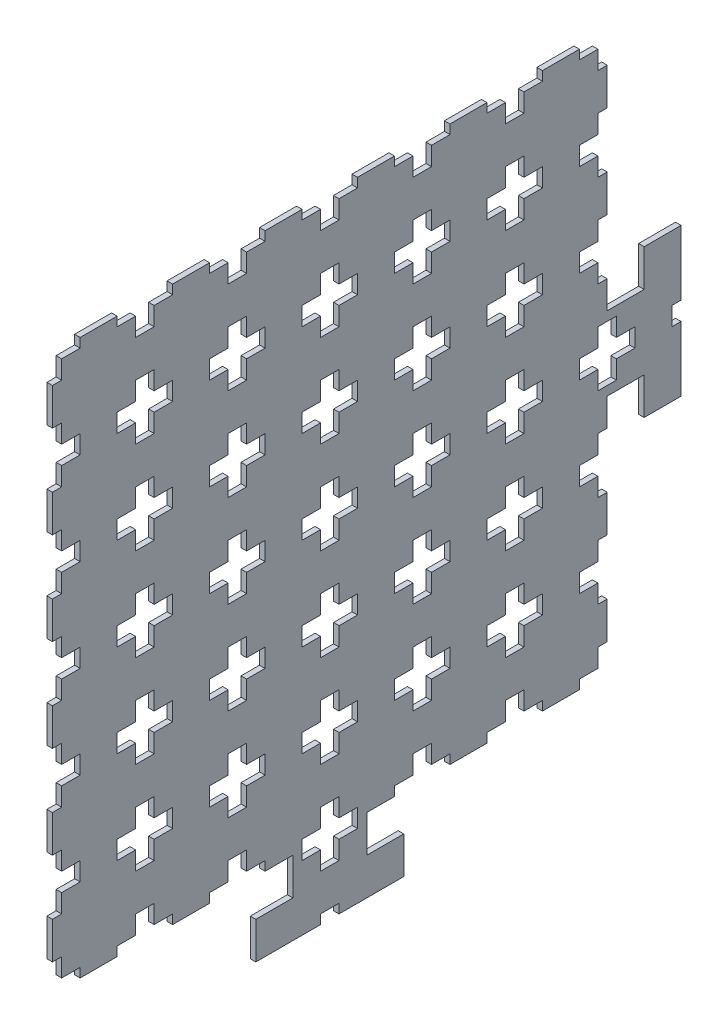
SolidWorks part; units mm, degrees
ref_plane "Plan de face" through (0, 0, 0) normal (0, 0, 1) x (1, 0, 0)
ref_plane "Plan de dessus" through (0, 0, 0) normal (0, 1, 0) x (1, 0, 0)
ref_plane "Plan de droite" through (0, 0, 0) normal (1, 0, 0) x (0, 0, -1)
sketch "Esquisse3" plane through (0, 0, 0) normal (1, 0, 0) x (0, 0, -1)
  line L0 (-540.6557, 133.6885) -> (-520.6557, 133.6885)
  line L1 (-540.6557, 133.6885) -> (-540.6557, 153.6885)
  line L2 (-540.6557, 153.6885) -> (-580.6557, 153.6885)
  line L3 (-580.6557, 133.6885) -> (-580.6557, 153.6885)
  line L4 (-520.6557, 133.6885) -> (-520.6557, 113.6885)
  line L5 (-710.6557, 453.6885) -> (-410.6557, 453.6885)
  line L6 (-710.6557, 453.6885) -> (-710.6557, 153.6885)
  line L7 (-710.6557, 153.6885) -> (-410.6557, 153.6885)
  line L8 (-410.6557, 453.6885) -> (-410.6557, 153.6885)
  line L9 (-520.6557, 113.6885) -> (-600.6557, 113.6885)
  line L10 (-600.6557, 113.6885) -> (-600.6557, 133.6885)
  line L11 (-600.6557, 133.6885) -> (-580.6557, 133.6885)
  line L12 (-710.6557, 153.6885) -> (-410.6557, 453.6885) construction
  line L13 (-410.6557, 153.6885) -> (-710.6557, 453.6885) construction
  line L14 (-410.6557, 323.6885) -> (-410.6557, 283.6885)
  line L15 (-390.6557, 323.6885) -> (-410.6557, 323.6885)
  line L16 (-390.6557, 323.6885) -> (-390.6557, 343.6885)
  line L17 (-390.6557, 343.6885) -> (-370.6557, 343.6885)
  line L18 (-370.6557, 343.6885) -> (-370.6557, 263.6885)
  line L19 (-370.6557, 263.6885) -> (-390.6557, 263.6885)
  line L20 (-390.6557, 263.6885) -> (-390.6557, 283.6885)
  line L21 (-390.6557, 283.6885) -> (-410.6557, 283.6885)
  point P12 (-560.6557, 303.6885)
  point P24 (-560.6557, 303.6885)
  dimension "D1" = 300
  dimension "D2" = 300
  dimension "D3" = 300
  dimension "D4" = 300
  dimension "D5" = 40
  dimension "D6" = 20
  dimension "D7" = 20
  dimension "D8" = 20
  dimension "D9" = 130
  dimension "D10" = 2
extrude "Boss.-Extru.1" add sketch "Esquisse3" along normal blind 3 contours L8 L5 L6 L7 | L11 L10 L9 L4 L0 L1 L2 L3 | L21 L20 L19 L18 L17 L16 L15 L8 region at (0, 130.3552, 560.6557) region at (0, 303.6885, 560.6557) region at (0, 303.6885, 387.3224)
sketch "Esquisse4" plane through (3, 0, 0) normal (1, 0, 0) x (0, 0, -1)
  line L1 (-710.6557, 453.6885) -> (-710.6557, 153.6885) construction
  line L2 (-505.6557, 198.6885) -> (-495.6557, 198.6885)
  line L3 (-515.6557, 188.6885) -> (-515.6557, 198.6885)
  line L4 (-515.6557, 188.6885) -> (-505.6557, 188.6885)
  line L5 (-505.6557, 188.6885) -> (-505.6557, 198.6885)
  line L6 (-495.6557, 198.6885) -> (-495.6557, 208.6885)
  line L7 (-495.6557, 208.6885) -> (-505.6557, 208.6885)
  line L8 (-505.6557, 208.6885) -> (-505.6557, 218.6885)
  line L9 (-505.6557, 218.6885) -> (-515.6557, 218.6885)
  line L10 (-515.6557, 218.6885) -> (-515.6557, 208.6885)
  line L11 (-515.6557, 208.6885) -> (-525.6557, 208.6885)
  line L12 (-525.6557, 208.6885) -> (-525.6557, 198.6885)
  line L13 (-525.6557, 198.6885) -> (-515.6557, 198.6885)
  line L14 (-455.6557, 198.6885) -> (-445.6557, 198.6885)
  line L15 (-465.6557, 188.6885) -> (-465.6557, 198.6885)
  line L16 (-465.6557, 188.6885) -> (-455.6557, 188.6885)
  line L17 (-455.6557, 188.6885) -> (-455.6557, 198.6885)
  line L18 (-445.6557, 198.6885) -> (-445.6557, 208.6885)
  line L19 (-445.6557, 208.6885) -> (-455.6557, 208.6885)
  line L20 (-455.6557, 208.6885) -> (-455.6557, 218.6885)
  line L21 (-455.6557, 218.6885) -> (-465.6557, 218.6885)
  line L22 (-465.6557, 218.6885) -> (-465.6557, 208.6885)
  line L23 (-465.6557, 208.6885) -> (-475.6557, 208.6885)
  line L24 (-475.6557, 208.6885) -> (-475.6557, 198.6885)
  line L25 (-475.6557, 198.6885) -> (-465.6557, 198.6885)
  line L26 (-405.6557, 198.6885) -> (-395.6557, 198.6885)
  line L27 (-415.6557, 188.6885) -> (-415.6557, 198.6885)
  line L29 (-555.6557, 198.6885) -> (-545.6557, 198.6885)
  line L30 (-415.6557, 188.6885) -> (-405.6557, 188.6885)
  line L31 (-565.6557, 188.6885) -> (-565.6557, 198.6885)
  line L32 (-565.6557, 188.6885) -> (-555.6557, 188.6885)
  line L33 (-555.6557, 188.6885) -> (-555.6557, 198.6885)
  line L34 (-545.6557, 198.6885) -> (-545.6557, 208.6885)
  line L35 (-545.6557, 208.6885) -> (-555.6557, 208.6885)
  line L36 (-555.6557, 208.6885) -> (-555.6557, 218.6885)
  line L37 (-555.6557, 218.6885) -> (-565.6557, 218.6885)
  line L38 (-565.6557, 218.6885) -> (-565.6557, 208.6885)
  line L39 (-565.6557, 208.6885) -> (-575.6557, 208.6885)
  line L40 (-575.6557, 208.6885) -> (-575.6557, 198.6885)
  line L41 (-575.6557, 198.6885) -> (-565.6557, 198.6885)
  line L42 (-405.6557, 188.6885) -> (-405.6557, 198.6885)
  line L43 (-395.6557, 198.6885) -> (-395.6557, 208.6885)
  line L44 (-395.6557, 208.6885) -> (-405.6557, 208.6885)
  line L45 (-405.6557, 208.6885) -> (-405.6557, 218.6885)
  line L46 (-405.6557, 218.6885) -> (-415.6557, 218.6885)
  line L47 (-415.6557, 218.6885) -> (-415.6557, 208.6885)
  line L48 (-415.6557, 208.6885) -> (-425.6557, 208.6885)
  line L49 (-425.6557, 208.6885) -> (-425.6557, 198.6885)
  line L50 (-425.6557, 198.6885) -> (-415.6557, 198.6885)
  line L51 (-555.6557, 198.6885) -> (-545.6557, 198.6885)
  line L52 (-565.6557, 188.6885) -> (-565.6557, 198.6885)
  line L53 (-565.6557, 188.6885) -> (-555.6557, 188.6885)
  line L54 (-555.6557, 188.6885) -> (-555.6557, 198.6885)
  line L55 (-545.6557, 198.6885) -> (-545.6557, 208.6885)
  line L56 (-545.6557, 208.6885) -> (-555.6557, 208.6885)
  line L57 (-555.6557, 208.6885) -> (-555.6557, 218.6885)
  line L58 (-555.6557, 218.6885) -> (-565.6557, 218.6885)
  line L59 (-565.6557, 218.6885) -> (-565.6557, 208.6885)
  line L60 (-565.6557, 208.6885) -> (-575.6557, 208.6885)
  line L61 (-575.6557, 208.6885) -> (-575.6557, 198.6885)
  line L62 (-575.6557, 198.6885) -> (-565.6557, 198.6885)
  line L63 (-505.6557, 198.6885) -> (-495.6557, 198.6885)
  line L64 (-515.6557, 188.6885) -> (-515.6557, 198.6885)
  line L65 (-515.6557, 188.6885) -> (-505.6557, 188.6885)
  line L66 (-505.6557, 188.6885) -> (-505.6557, 198.6885)
  line L67 (-495.6557, 198.6885) -> (-495.6557, 208.6885)
  line L68 (-495.6557, 208.6885) -> (-505.6557, 208.6885)
  line L69 (-505.6557, 208.6885) -> (-505.6557, 218.6885)
  line L70 (-505.6557, 218.6885) -> (-515.6557, 218.6885)
  line L71 (-515.6557, 218.6885) -> (-515.6557, 208.6885)
  line L72 (-515.6557, 208.6885) -> (-525.6557, 208.6885)
  line L73 (-525.6557, 208.6885) -> (-525.6557, 198.6885)
  line L74 (-525.6557, 198.6885) -> (-515.6557, 198.6885)
  line L75 (-455.6557, 198.6885) -> (-445.6557, 198.6885)
  line L76 (-465.6557, 188.6885) -> (-465.6557, 198.6885)
  line L77 (-465.6557, 188.6885) -> (-455.6557, 188.6885)
  line L78 (-455.6557, 188.6885) -> (-455.6557, 198.6885)
  line L79 (-445.6557, 198.6885) -> (-445.6557, 208.6885)
  line L80 (-445.6557, 208.6885) -> (-455.6557, 208.6885)
  line L81 (-455.6557, 208.6885) -> (-455.6557, 218.6885)
  line L82 (-455.6557, 218.6885) -> (-465.6557, 218.6885)
  line L83 (-465.6557, 218.6885) -> (-465.6557, 208.6885)
  line L84 (-465.6557, 208.6885) -> (-475.6557, 208.6885)
  line L85 (-475.6557, 208.6885) -> (-475.6557, 198.6885)
  line L86 (-475.6557, 198.6885) -> (-465.6557, 198.6885)
  line L87 (-605.6557, 198.6885) -> (-595.6557, 198.6885)
  line L88 (-615.6557, 188.6885) -> (-615.6557, 198.6885)
  line L89 (-615.6557, 188.6885) -> (-605.6557, 188.6885)
  line L90 (-605.6557, 188.6885) -> (-605.6557, 198.6885)
  line L91 (-595.6557, 198.6885) -> (-595.6557, 208.6885)
  line L92 (-595.6557, 208.6885) -> (-605.6557, 208.6885)
  line L93 (-605.6557, 208.6885) -> (-605.6557, 218.6885)
  line L94 (-605.6557, 218.6885) -> (-615.6557, 218.6885)
  line L95 (-615.6557, 218.6885) -> (-615.6557, 208.6885)
  line L96 (-615.6557, 208.6885) -> (-625.6557, 208.6885)
  line L97 (-625.6557, 208.6885) -> (-625.6557, 198.6885)
  line L98 (-625.6557, 198.6885) -> (-615.6557, 198.6885)
  line L99 (-555.6557, 198.6885) -> (-545.6557, 198.6885)
  line L100 (-565.6557, 188.6885) -> (-565.6557, 198.6885)
  line L101 (-565.6557, 188.6885) -> (-555.6557, 188.6885)
  line L102 (-555.6557, 188.6885) -> (-555.6557, 198.6885)
  line L103 (-545.6557, 198.6885) -> (-545.6557, 208.6885)
  line L104 (-545.6557, 208.6885) -> (-555.6557, 208.6885)
  line L105 (-555.6557, 208.6885) -> (-555.6557, 218.6885)
  line L106 (-555.6557, 218.6885) -> (-565.6557, 218.6885)
  line L107 (-565.6557, 218.6885) -> (-565.6557, 208.6885)
  line L108 (-565.6557, 208.6885) -> (-575.6557, 208.6885)
  line L109 (-575.6557, 208.6885) -> (-575.6557, 198.6885)
  line L110 (-575.6557, 198.6885) -> (-565.6557, 198.6885)
  line L111 (-505.6557, 198.6885) -> (-495.6557, 198.6885)
  line L112 (-515.6557, 188.6885) -> (-515.6557, 198.6885)
  line L113 (-515.6557, 188.6885) -> (-505.6557, 188.6885)
  line L114 (-505.6557, 188.6885) -> (-505.6557, 198.6885)
  line L115 (-495.6557, 198.6885) -> (-495.6557, 208.6885)
  line L116 (-495.6557, 208.6885) -> (-505.6557, 208.6885)
  line L117 (-505.6557, 208.6885) -> (-505.6557, 218.6885)
  line L118 (-505.6557, 218.6885) -> (-515.6557, 218.6885)
  line L119 (-515.6557, 218.6885) -> (-515.6557, 208.6885)
  line L120 (-515.6557, 208.6885) -> (-525.6557, 208.6885)
  line L121 (-525.6557, 208.6885) -> (-525.6557, 198.6885)
  line L122 (-525.6557, 198.6885) -> (-515.6557, 198.6885)
  line L123 (-655.6557, 198.6885) -> (-645.6557, 198.6885)
  line L124 (-665.6557, 188.6885) -> (-665.6557, 198.6885)
  line L125 (-665.6557, 188.6885) -> (-655.6557, 188.6885)
  line L126 (-655.6557, 188.6885) -> (-655.6557, 198.6885)
  line L127 (-645.6557, 198.6885) -> (-645.6557, 208.6885)
  line L128 (-645.6557, 208.6885) -> (-655.6557, 208.6885)
  line L129 (-655.6557, 208.6885) -> (-655.6557, 218.6885)
  line L130 (-655.6557, 218.6885) -> (-665.6557, 218.6885)
  line L131 (-665.6557, 218.6885) -> (-665.6557, 208.6885)
  line L132 (-665.6557, 208.6885) -> (-675.6557, 208.6885)
  line L133 (-675.6557, 208.6885) -> (-675.6557, 198.6885)
  line L134 (-675.6557, 198.6885) -> (-665.6557, 198.6885)
  line L135 (-605.6557, 198.6885) -> (-595.6557, 198.6885)
  line L136 (-615.6557, 188.6885) -> (-615.6557, 198.6885)
  line L137 (-615.6557, 188.6885) -> (-605.6557, 188.6885)
  line L138 (-605.6557, 188.6885) -> (-605.6557, 198.6885)
  line L139 (-595.6557, 198.6885) -> (-595.6557, 208.6885)
  line L140 (-595.6557, 208.6885) -> (-605.6557, 208.6885)
  line L141 (-605.6557, 208.6885) -> (-605.6557, 218.6885)
  line L142 (-605.6557, 218.6885) -> (-615.6557, 218.6885)
  line L143 (-615.6557, 218.6885) -> (-615.6557, 208.6885)
  line L144 (-615.6557, 208.6885) -> (-625.6557, 208.6885)
  line L145 (-625.6557, 208.6885) -> (-625.6557, 198.6885)
  line L146 (-625.6557, 198.6885) -> (-615.6557, 198.6885)
  line L147 (-555.6557, 198.6885) -> (-545.6557, 198.6885)
  line L148 (-565.6557, 188.6885) -> (-565.6557, 198.6885)
  line L149 (-565.6557, 188.6885) -> (-555.6557, 188.6885)
  line L150 (-555.6557, 188.6885) -> (-555.6557, 198.6885)
  line L151 (-545.6557, 198.6885) -> (-545.6557, 208.6885)
  line L152 (-545.6557, 208.6885) -> (-555.6557, 208.6885)
  line L153 (-555.6557, 208.6885) -> (-555.6557, 218.6885)
  line L154 (-555.6557, 218.6885) -> (-565.6557, 218.6885)
  line L155 (-565.6557, 218.6885) -> (-565.6557, 208.6885)
  line L156 (-565.6557, 208.6885) -> (-575.6557, 208.6885)
  line L157 (-575.6557, 208.6885) -> (-575.6557, 198.6885)
  line L158 (-575.6557, 198.6885) -> (-565.6557, 198.6885)
  line L159 (-605.6557, 198.6885) -> (-595.6557, 198.6885)
  line L160 (-615.6557, 188.6885) -> (-615.6557, 198.6885)
  line L161 (-615.6557, 188.6885) -> (-605.6557, 188.6885)
  line L162 (-605.6557, 188.6885) -> (-605.6557, 198.6885)
  line L163 (-595.6557, 198.6885) -> (-595.6557, 208.6885)
  line L164 (-595.6557, 208.6885) -> (-605.6557, 208.6885)
  line L165 (-605.6557, 208.6885) -> (-605.6557, 218.6885)
  line L166 (-605.6557, 218.6885) -> (-615.6557, 218.6885)
  line L167 (-615.6557, 218.6885) -> (-615.6557, 208.6885)
  line L168 (-615.6557, 208.6885) -> (-625.6557, 208.6885)
  line L169 (-625.6557, 208.6885) -> (-625.6557, 198.6885)
  line L170 (-625.6557, 198.6885) -> (-615.6557, 198.6885)
  line L171 (-655.6557, 198.6885) -> (-645.6557, 198.6885)
  line L172 (-665.6557, 188.6885) -> (-665.6557, 198.6885)
  line L173 (-665.6557, 188.6885) -> (-655.6557, 188.6885)
  line L174 (-655.6557, 188.6885) -> (-655.6557, 198.6885)
  line L175 (-645.6557, 198.6885) -> (-645.6557, 208.6885)
  line L176 (-645.6557, 208.6885) -> (-655.6557, 208.6885)
  line L177 (-655.6557, 208.6885) -> (-655.6557, 218.6885)
  line L178 (-655.6557, 218.6885) -> (-665.6557, 218.6885)
  line L179 (-665.6557, 218.6885) -> (-665.6557, 208.6885)
  line L180 (-665.6557, 208.6885) -> (-675.6557, 208.6885)
  line L181 (-675.6557, 208.6885) -> (-675.6557, 198.6885)
  line L182 (-675.6557, 198.6885) -> (-665.6557, 198.6885)
  line L183 (-705.6557, 198.6885) -> (-695.6557, 198.6885)
  line L184 (-715.6557, 188.6885) -> (-715.6557, 198.6885)
  line L185 (-715.6557, 188.6885) -> (-705.6557, 188.6885)
  line L186 (-705.6557, 188.6885) -> (-705.6557, 198.6885)
  line L187 (-695.6557, 198.6885) -> (-695.6557, 208.6885)
  line L188 (-695.6557, 208.6885) -> (-705.6557, 208.6885)
  line L189 (-705.6557, 208.6885) -> (-705.6557, 218.6885)
  line L190 (-705.6557, 218.6885) -> (-715.6557, 218.6885)
  line L191 (-715.6557, 218.6885) -> (-715.6557, 208.6885)
  line L192 (-715.6557, 208.6885) -> (-725.6557, 208.6885)
  line L193 (-725.6557, 208.6885) -> (-725.6557, 198.6885)
  line L194 (-725.6557, 198.6885) -> (-715.6557, 198.6885)
  line L195 (-505.6557, 148.6885) -> (-495.6557, 148.6885)
  line L196 (-515.6557, 138.6885) -> (-515.6557, 148.6885)
  line L197 (-515.6557, 138.6885) -> (-505.6557, 138.6885)
  line L198 (-505.6557, 138.6885) -> (-505.6557, 148.6885)
  line L199 (-495.6557, 148.6885) -> (-495.6557, 158.6885)
  line L200 (-495.6557, 158.6885) -> (-505.6557, 158.6885)
  line L201 (-505.6557, 158.6885) -> (-505.6557, 168.6885)
  line L202 (-505.6557, 168.6885) -> (-515.6557, 168.6885)
  line L203 (-515.6557, 168.6885) -> (-515.6557, 158.6885)
  line L204 (-515.6557, 158.6885) -> (-525.6557, 158.6885)
  line L205 (-525.6557, 158.6885) -> (-525.6557, 148.6885)
  line L206 (-525.6557, 148.6885) -> (-515.6557, 148.6885)
  line L207 (-455.6557, 148.6885) -> (-445.6557, 148.6885)
  line L208 (-465.6557, 138.6885) -> (-465.6557, 148.6885)
  line L209 (-465.6557, 138.6885) -> (-455.6557, 138.6885)
  line L210 (-455.6557, 138.6885) -> (-455.6557, 148.6885)
  line L211 (-445.6557, 148.6885) -> (-445.6557, 158.6885)
  line L212 (-445.6557, 158.6885) -> (-455.6557, 158.6885)
  line L213 (-455.6557, 158.6885) -> (-455.6557, 168.6885)
  line L214 (-455.6557, 168.6885) -> (-465.6557, 168.6885)
  line L215 (-465.6557, 168.6885) -> (-465.6557, 158.6885)
  line L216 (-465.6557, 158.6885) -> (-475.6557, 158.6885)
  line L217 (-475.6557, 158.6885) -> (-475.6557, 148.6885)
  line L218 (-475.6557, 148.6885) -> (-465.6557, 148.6885)
  line L219 (-405.6557, 148.6885) -> (-395.6557, 148.6885)
  line L220 (-415.6557, 138.6885) -> (-415.6557, 148.6885)
  line L221 (-555.6557, 148.6885) -> (-545.6557, 148.6885)
  line L222 (-415.6557, 138.6885) -> (-405.6557, 138.6885)
  line L223 (-565.6557, 138.6885) -> (-565.6557, 148.6885)
  line L224 (-565.6557, 138.6885) -> (-555.6557, 138.6885)
  line L225 (-555.6557, 138.6885) -> (-555.6557, 148.6885)
  line L226 (-545.6557, 148.6885) -> (-545.6557, 158.6885)
  line L227 (-545.6557, 158.6885) -> (-555.6557, 158.6885)
  line L228 (-555.6557, 158.6885) -> (-555.6557, 168.6885)
  line L229 (-555.6557, 168.6885) -> (-565.6557, 168.6885)
  line L230 (-565.6557, 168.6885) -> (-565.6557, 158.6885)
  line L231 (-565.6557, 158.6885) -> (-575.6557, 158.6885)
  line L232 (-575.6557, 158.6885) -> (-575.6557, 148.6885)
  line L233 (-575.6557, 148.6885) -> (-565.6557, 148.6885)
  line L234 (-405.6557, 138.6885) -> (-405.6557, 148.6885)
  line L235 (-395.6557, 148.6885) -> (-395.6557, 158.6885)
  line L236 (-395.6557, 158.6885) -> (-405.6557, 158.6885)
  line L237 (-405.6557, 158.6885) -> (-405.6557, 168.6885)
  line L238 (-405.6557, 168.6885) -> (-415.6557, 168.6885)
  line L239 (-415.6557, 168.6885) -> (-415.6557, 158.6885)
  line L240 (-415.6557, 158.6885) -> (-425.6557, 158.6885)
  line L241 (-425.6557, 158.6885) -> (-425.6557, 148.6885)
  line L242 (-425.6557, 148.6885) -> (-415.6557, 148.6885)
  line L243 (-555.6557, 148.6885) -> (-545.6557, 148.6885)
  line L244 (-565.6557, 138.6885) -> (-565.6557, 148.6885)
  line L245 (-565.6557, 138.6885) -> (-555.6557, 138.6885)
  line L246 (-555.6557, 138.6885) -> (-555.6557, 148.6885)
  line L247 (-545.6557, 148.6885) -> (-545.6557, 158.6885)
  line L248 (-545.6557, 158.6885) -> (-555.6557, 158.6885)
  line L249 (-555.6557, 158.6885) -> (-555.6557, 168.6885)
  line L250 (-555.6557, 168.6885) -> (-565.6557, 168.6885)
  line L251 (-565.6557, 168.6885) -> (-565.6557, 158.6885)
  line L252 (-565.6557, 158.6885) -> (-575.6557, 158.6885)
  line L253 (-575.6557, 158.6885) -> (-575.6557, 148.6885)
  line L254 (-575.6557, 148.6885) -> (-565.6557, 148.6885)
  line L255 (-505.6557, 148.6885) -> (-495.6557, 148.6885)
  line L256 (-515.6557, 138.6885) -> (-515.6557, 148.6885)
  line L257 (-515.6557, 138.6885) -> (-505.6557, 138.6885)
  line L258 (-505.6557, 138.6885) -> (-505.6557, 148.6885)
  line L259 (-495.6557, 148.6885) -> (-495.6557, 158.6885)
  line L260 (-495.6557, 158.6885) -> (-505.6557, 158.6885)
  line L261 (-505.6557, 158.6885) -> (-505.6557, 168.6885)
  line L262 (-505.6557, 168.6885) -> (-515.6557, 168.6885)
  line L263 (-515.6557, 168.6885) -> (-515.6557, 158.6885)
  line L264 (-515.6557, 158.6885) -> (-525.6557, 158.6885)
  line L265 (-525.6557, 158.6885) -> (-525.6557, 148.6885)
  line L266 (-525.6557, 148.6885) -> (-515.6557, 148.6885)
  line L267 (-455.6557, 148.6885) -> (-445.6557, 148.6885)
  line L268 (-465.6557, 138.6885) -> (-465.6557, 148.6885)
  line L269 (-465.6557, 138.6885) -> (-455.6557, 138.6885)
  line L270 (-455.6557, 138.6885) -> (-455.6557, 148.6885)
  line L271 (-445.6557, 148.6885) -> (-445.6557, 158.6885)
  line L272 (-445.6557, 158.6885) -> (-455.6557, 158.6885)
  line L273 (-455.6557, 158.6885) -> (-455.6557, 168.6885)
  line L274 (-455.6557, 168.6885) -> (-465.6557, 168.6885)
  line L275 (-465.6557, 168.6885) -> (-465.6557, 158.6885)
  line L276 (-465.6557, 158.6885) -> (-475.6557, 158.6885)
  line L277 (-475.6557, 158.6885) -> (-475.6557, 148.6885)
  line L278 (-475.6557, 148.6885) -> (-465.6557, 148.6885)
  line L279 (-605.6557, 148.6885) -> (-595.6557, 148.6885)
  line L280 (-615.6557, 138.6885) -> (-615.6557, 148.6885)
  line L281 (-615.6557, 138.6885) -> (-605.6557, 138.6885)
  line L282 (-605.6557, 138.6885) -> (-605.6557, 148.6885)
  line L283 (-595.6557, 148.6885) -> (-595.6557, 158.6885)
  line L284 (-595.6557, 158.6885) -> (-605.6557, 158.6885)
  line L285 (-605.6557, 158.6885) -> (-605.6557, 168.6885)
  line L286 (-605.6557, 168.6885) -> (-615.6557, 168.6885)
  line L287 (-615.6557, 168.6885) -> (-615.6557, 158.6885)
  line L288 (-615.6557, 158.6885) -> (-625.6557, 158.6885)
  line L289 (-625.6557, 158.6885) -> (-625.6557, 148.6885)
  line L290 (-625.6557, 148.6885) -> (-615.6557, 148.6885)
  line L291 (-555.6557, 148.6885) -> (-545.6557, 148.6885)
  line L292 (-565.6557, 138.6885) -> (-565.6557, 148.6885)
  line L293 (-565.6557, 138.6885) -> (-555.6557, 138.6885)
  line L294 (-555.6557, 138.6885) -> (-555.6557, 148.6885)
  line L295 (-545.6557, 148.6885) -> (-545.6557, 158.6885)
  line L296 (-545.6557, 158.6885) -> (-555.6557, 158.6885)
  line L297 (-555.6557, 158.6885) -> (-555.6557, 168.6885)
  line L298 (-555.6557, 168.6885) -> (-565.6557, 168.6885)
  line L299 (-565.6557, 168.6885) -> (-565.6557, 158.6885)
  line L300 (-565.6557, 158.6885) -> (-575.6557, 158.6885)
  line L301 (-575.6557, 158.6885) -> (-575.6557, 148.6885)
  line L302 (-575.6557, 148.6885) -> (-565.6557, 148.6885)
  line L303 (-505.6557, 148.6885) -> (-495.6557, 148.6885)
  line L304 (-515.6557, 138.6885) -> (-515.6557, 148.6885)
  line L305 (-515.6557, 138.6885) -> (-505.6557, 138.6885)
  line L306 (-505.6557, 138.6885) -> (-505.6557, 148.6885)
  line L307 (-495.6557, 148.6885) -> (-495.6557, 158.6885)
  line L308 (-495.6557, 158.6885) -> (-505.6557, 158.6885)
  line L309 (-505.6557, 158.6885) -> (-505.6557, 168.6885)
  line L310 (-505.6557, 168.6885) -> (-515.6557, 168.6885)
  line L311 (-515.6557, 168.6885) -> (-515.6557, 158.6885)
  line L312 (-515.6557, 158.6885) -> (-525.6557, 158.6885)
  line L313 (-525.6557, 158.6885) -> (-525.6557, 148.6885)
  line L314 (-525.6557, 148.6885) -> (-515.6557, 148.6885)
  line L315 (-655.6557, 148.6885) -> (-645.6557, 148.6885)
  line L316 (-665.6557, 138.6885) -> (-665.6557, 148.6885)
  line L317 (-665.6557, 138.6885) -> (-655.6557, 138.6885)
  line L318 (-655.6557, 138.6885) -> (-655.6557, 148.6885)
  line L319 (-645.6557, 148.6885) -> (-645.6557, 158.6885)
  line L320 (-645.6557, 158.6885) -> (-655.6557, 158.6885)
  line L321 (-655.6557, 158.6885) -> (-655.6557, 168.6885)
  line L322 (-655.6557, 168.6885) -> (-665.6557, 168.6885)
  line L323 (-665.6557, 168.6885) -> (-665.6557, 158.6885)
  line L324 (-665.6557, 158.6885) -> (-675.6557, 158.6885)
  line L325 (-675.6557, 158.6885) -> (-675.6557, 148.6885)
  line L326 (-675.6557, 148.6885) -> (-665.6557, 148.6885)
  line L327 (-605.6557, 148.6885) -> (-595.6557, 148.6885)
  line L328 (-615.6557, 138.6885) -> (-615.6557, 148.6885)
  line L329 (-615.6557, 138.6885) -> (-605.6557, 138.6885)
  line L330 (-605.6557, 138.6885) -> (-605.6557, 148.6885)
  line L331 (-595.6557, 148.6885) -> (-595.6557, 158.6885)
  line L332 (-595.6557, 158.6885) -> (-605.6557, 158.6885)
  line L333 (-605.6557, 158.6885) -> (-605.6557, 168.6885)
  line L334 (-605.6557, 168.6885) -> (-615.6557, 168.6885)
  line L335 (-615.6557, 168.6885) -> (-615.6557, 158.6885)
  line L336 (-615.6557, 158.6885) -> (-625.6557, 158.6885)
  line L337 (-625.6557, 158.6885) -> (-625.6557, 148.6885)
  line L338 (-625.6557, 148.6885) -> (-615.6557, 148.6885)
  line L339 (-555.6557, 148.6885) -> (-545.6557, 148.6885)
  line L340 (-565.6557, 138.6885) -> (-565.6557, 148.6885)
  line L341 (-565.6557, 138.6885) -> (-555.6557, 138.6885)
  line L342 (-555.6557, 138.6885) -> (-555.6557, 148.6885)
  line L343 (-545.6557, 148.6885) -> (-545.6557, 158.6885)
  line L344 (-545.6557, 158.6885) -> (-555.6557, 158.6885)
  line L345 (-555.6557, 158.6885) -> (-555.6557, 168.6885)
  line L346 (-555.6557, 168.6885) -> (-565.6557, 168.6885)
  line L347 (-565.6557, 168.6885) -> (-565.6557, 158.6885)
  line L348 (-565.6557, 158.6885) -> (-575.6557, 158.6885)
  line L349 (-575.6557, 158.6885) -> (-575.6557, 148.6885)
  line L350 (-575.6557, 148.6885) -> (-565.6557, 148.6885)
  line L351 (-605.6557, 148.6885) -> (-595.6557, 148.6885)
  line L352 (-615.6557, 138.6885) -> (-615.6557, 148.6885)
  line L353 (-615.6557, 138.6885) -> (-605.6557, 138.6885)
  line L354 (-605.6557, 138.6885) -> (-605.6557, 148.6885)
  line L355 (-595.6557, 148.6885) -> (-595.6557, 158.6885)
  line L356 (-595.6557, 158.6885) -> (-605.6557, 158.6885)
  line L357 (-605.6557, 158.6885) -> (-605.6557, 168.6885)
  line L358 (-605.6557, 168.6885) -> (-615.6557, 168.6885)
  line L359 (-615.6557, 168.6885) -> (-615.6557, 158.6885)
  line L360 (-615.6557, 158.6885) -> (-625.6557, 158.6885)
  line L361 (-625.6557, 158.6885) -> (-625.6557, 148.6885)
  line L362 (-625.6557, 148.6885) -> (-615.6557, 148.6885)
  line L363 (-655.6557, 148.6885) -> (-645.6557, 148.6885)
  line L364 (-665.6557, 138.6885) -> (-665.6557, 148.6885)
  line L365 (-665.6557, 138.6885) -> (-655.6557, 138.6885)
  line L366 (-655.6557, 138.6885) -> (-655.6557, 148.6885)
  line L367 (-645.6557, 148.6885) -> (-645.6557, 158.6885)
  line L368 (-645.6557, 158.6885) -> (-655.6557, 158.6885)
  line L369 (-655.6557, 158.6885) -> (-655.6557, 168.6885)
  line L370 (-655.6557, 168.6885) -> (-665.6557, 168.6885)
  line L371 (-665.6557, 168.6885) -> (-665.6557, 158.6885)
  line L372 (-665.6557, 158.6885) -> (-675.6557, 158.6885)
  line L373 (-675.6557, 158.6885) -> (-675.6557, 148.6885)
  line L374 (-675.6557, 148.6885) -> (-665.6557, 148.6885)
  line L375 (-705.6557, 148.6885) -> (-695.6557, 148.6885)
  line L376 (-715.6557, 138.6885) -> (-715.6557, 148.6885)
  line L377 (-715.6557, 138.6885) -> (-705.6557, 138.6885)
  line L378 (-705.6557, 138.6885) -> (-705.6557, 148.6885)
  line L379 (-695.6557, 148.6885) -> (-695.6557, 158.6885)
  line L380 (-695.6557, 158.6885) -> (-705.6557, 158.6885)
  line L381 (-705.6557, 158.6885) -> (-705.6557, 168.6885)
  line L382 (-705.6557, 168.6885) -> (-715.6557, 168.6885)
  line L383 (-715.6557, 168.6885) -> (-715.6557, 158.6885)
  line L384 (-715.6557, 158.6885) -> (-725.6557, 158.6885)
  line L385 (-725.6557, 158.6885) -> (-725.6557, 148.6885)
  line L386 (-725.6557, 148.6885) -> (-715.6557, 148.6885)
  line L387 (-505.6557, 198.6885) -> (-495.6557, 198.6885)
  line L388 (-515.6557, 188.6885) -> (-515.6557, 198.6885)
  line L389 (-515.6557, 188.6885) -> (-505.6557, 188.6885)
  line L390 (-505.6557, 188.6885) -> (-505.6557, 198.6885)
  line L391 (-495.6557, 198.6885) -> (-495.6557, 208.6885)
  line L392 (-495.6557, 208.6885) -> (-505.6557, 208.6885)
  line L393 (-505.6557, 208.6885) -> (-505.6557, 218.6885)
  line L394 (-505.6557, 218.6885) -> (-515.6557, 218.6885)
  line L395 (-515.6557, 218.6885) -> (-515.6557, 208.6885)
  line L396 (-515.6557, 208.6885) -> (-525.6557, 208.6885)
  line L397 (-525.6557, 208.6885) -> (-525.6557, 198.6885)
  line L398 (-525.6557, 198.6885) -> (-515.6557, 198.6885)
  line L399 (-455.6557, 198.6885) -> (-445.6557, 198.6885)
  line L400 (-465.6557, 188.6885) -> (-465.6557, 198.6885)
  line L401 (-465.6557, 188.6885) -> (-455.6557, 188.6885)
  line L402 (-455.6557, 188.6885) -> (-455.6557, 198.6885)
  line L403 (-445.6557, 198.6885) -> (-445.6557, 208.6885)
  line L404 (-445.6557, 208.6885) -> (-455.6557, 208.6885)
  line L405 (-455.6557, 208.6885) -> (-455.6557, 218.6885)
  line L406 (-455.6557, 218.6885) -> (-465.6557, 218.6885)
  line L407 (-465.6557, 218.6885) -> (-465.6557, 208.6885)
  line L408 (-465.6557, 208.6885) -> (-475.6557, 208.6885)
  line L409 (-475.6557, 208.6885) -> (-475.6557, 198.6885)
  line L410 (-475.6557, 198.6885) -> (-465.6557, 198.6885)
  line L411 (-405.6557, 198.6885) -> (-395.6557, 198.6885)
  line L412 (-415.6557, 188.6885) -> (-415.6557, 198.6885)
  line L413 (-555.6557, 198.6885) -> (-545.6557, 198.6885)
  line L414 (-415.6557, 188.6885) -> (-405.6557, 188.6885)
  line L415 (-565.6557, 188.6885) -> (-565.6557, 198.6885)
  line L416 (-565.6557, 188.6885) -> (-555.6557, 188.6885)
  line L417 (-555.6557, 188.6885) -> (-555.6557, 198.6885)
  line L418 (-545.6557, 198.6885) -> (-545.6557, 208.6885)
  line L419 (-545.6557, 208.6885) -> (-555.6557, 208.6885)
  line L420 (-555.6557, 208.6885) -> (-555.6557, 218.6885)
  line L421 (-555.6557, 218.6885) -> (-565.6557, 218.6885)
  line L422 (-565.6557, 218.6885) -> (-565.6557, 208.6885)
  line L423 (-565.6557, 208.6885) -> (-575.6557, 208.6885)
  line L424 (-575.6557, 208.6885) -> (-575.6557, 198.6885)
  line L425 (-575.6557, 198.6885) -> (-565.6557, 198.6885)
  line L426 (-405.6557, 188.6885) -> (-405.6557, 198.6885)
  line L427 (-395.6557, 198.6885) -> (-395.6557, 208.6885)
  line L428 (-395.6557, 208.6885) -> (-405.6557, 208.6885)
  line L429 (-405.6557, 208.6885) -> (-405.6557, 218.6885)
  line L430 (-405.6557, 218.6885) -> (-415.6557, 218.6885)
  line L431 (-415.6557, 218.6885) -> (-415.6557, 208.6885)
  line L432 (-415.6557, 208.6885) -> (-425.6557, 208.6885)
  line L433 (-425.6557, 208.6885) -> (-425.6557, 198.6885)
  line L434 (-425.6557, 198.6885) -> (-415.6557, 198.6885)
  line L435 (-555.6557, 198.6885) -> (-545.6557, 198.6885)
  line L436 (-565.6557, 188.6885) -> (-565.6557, 198.6885)
  line L437 (-565.6557, 188.6885) -> (-555.6557, 188.6885)
  line L438 (-555.6557, 188.6885) -> (-555.6557, 198.6885)
  line L439 (-545.6557, 198.6885) -> (-545.6557, 208.6885)
  line L440 (-545.6557, 208.6885) -> (-555.6557, 208.6885)
  line L441 (-555.6557, 208.6885) -> (-555.6557, 218.6885)
  line L442 (-555.6557, 218.6885) -> (-565.6557, 218.6885)
  line L443 (-565.6557, 218.6885) -> (-565.6557, 208.6885)
  line L444 (-565.6557, 208.6885) -> (-575.6557, 208.6885)
  line L445 (-575.6557, 208.6885) -> (-575.6557, 198.6885)
  line L446 (-575.6557, 198.6885) -> (-565.6557, 198.6885)
  line L447 (-505.6557, 198.6885) -> (-495.6557, 198.6885)
  line L448 (-515.6557, 188.6885) -> (-515.6557, 198.6885)
  line L449 (-515.6557, 188.6885) -> (-505.6557, 188.6885)
  line L450 (-505.6557, 188.6885) -> (-505.6557, 198.6885)
  line L451 (-495.6557, 198.6885) -> (-495.6557, 208.6885)
  line L452 (-495.6557, 208.6885) -> (-505.6557, 208.6885)
  line L453 (-505.6557, 208.6885) -> (-505.6557, 218.6885)
  line L454 (-505.6557, 218.6885) -> (-515.6557, 218.6885)
  line L455 (-515.6557, 218.6885) -> (-515.6557, 208.6885)
  line L456 (-515.6557, 208.6885) -> (-525.6557, 208.6885)
  line L457 (-525.6557, 208.6885) -> (-525.6557, 198.6885)
  line L458 (-525.6557, 198.6885) -> (-515.6557, 198.6885)
  line L459 (-455.6557, 198.6885) -> (-445.6557, 198.6885)
  line L460 (-465.6557, 188.6885) -> (-465.6557, 198.6885)
  line L461 (-465.6557, 188.6885) -> (-455.6557, 188.6885)
  line L462 (-455.6557, 188.6885) -> (-455.6557, 198.6885)
  line L463 (-445.6557, 198.6885) -> (-445.6557, 208.6885)
  line L464 (-445.6557, 208.6885) -> (-455.6557, 208.6885)
  line L465 (-455.6557, 208.6885) -> (-455.6557, 218.6885)
  line L466 (-455.6557, 218.6885) -> (-465.6557, 218.6885)
  line L467 (-465.6557, 218.6885) -> (-465.6557, 208.6885)
  line L468 (-465.6557, 208.6885) -> (-475.6557, 208.6885)
  line L469 (-475.6557, 208.6885) -> (-475.6557, 198.6885)
  line L470 (-475.6557, 198.6885) -> (-465.6557, 198.6885)
  line L471 (-605.6557, 198.6885) -> (-595.6557, 198.6885)
  line L472 (-615.6557, 188.6885) -> (-615.6557, 198.6885)
  line L473 (-615.6557, 188.6885) -> (-605.6557, 188.6885)
  line L474 (-605.6557, 188.6885) -> (-605.6557, 198.6885)
  line L475 (-595.6557, 198.6885) -> (-595.6557, 208.6885)
  line L476 (-595.6557, 208.6885) -> (-605.6557, 208.6885)
  line L477 (-605.6557, 208.6885) -> (-605.6557, 218.6885)
  line L478 (-605.6557, 218.6885) -> (-615.6557, 218.6885)
  line L479 (-615.6557, 218.6885) -> (-615.6557, 208.6885)
  line L480 (-615.6557, 208.6885) -> (-625.6557, 208.6885)
  line L481 (-625.6557, 208.6885) -> (-625.6557, 198.6885)
  line L482 (-625.6557, 198.6885) -> (-615.6557, 198.6885)
  line L483 (-555.6557, 198.6885) -> (-545.6557, 198.6885)
  line L484 (-565.6557, 188.6885) -> (-565.6557, 198.6885)
  line L485 (-565.6557, 188.6885) -> (-555.6557, 188.6885)
  line L486 (-555.6557, 188.6885) -> (-555.6557, 198.6885)
  line L487 (-545.6557, 198.6885) -> (-545.6557, 208.6885)
  line L488 (-545.6557, 208.6885) -> (-555.6557, 208.6885)
  line L489 (-555.6557, 208.6885) -> (-555.6557, 218.6885)
  line L490 (-555.6557, 218.6885) -> (-565.6557, 218.6885)
  line L491 (-565.6557, 218.6885) -> (-565.6557, 208.6885)
  line L492 (-565.6557, 208.6885) -> (-575.6557, 208.6885)
  line L493 (-575.6557, 208.6885) -> (-575.6557, 198.6885)
  line L494 (-575.6557, 198.6885) -> (-565.6557, 198.6885)
  line L495 (-505.6557, 198.6885) -> (-495.6557, 198.6885)
  line L496 (-515.6557, 188.6885) -> (-515.6557, 198.6885)
  line L497 (-515.6557, 188.6885) -> (-505.6557, 188.6885)
  line L498 (-505.6557, 188.6885) -> (-505.6557, 198.6885)
  line L499 (-495.6557, 198.6885) -> (-495.6557, 208.6885)
  line L500 (-495.6557, 208.6885) -> (-505.6557, 208.6885)
  line L501 (-505.6557, 208.6885) -> (-505.6557, 218.6885)
  line L502 (-505.6557, 218.6885) -> (-515.6557, 218.6885)
  line L503 (-515.6557, 218.6885) -> (-515.6557, 208.6885)
  line L504 (-515.6557, 208.6885) -> (-525.6557, 208.6885)
  line L505 (-525.6557, 208.6885) -> (-525.6557, 198.6885)
  line L506 (-525.6557, 198.6885) -> (-515.6557, 198.6885)
  line L507 (-655.6557, 198.6885) -> (-645.6557, 198.6885)
  line L508 (-665.6557, 188.6885) -> (-665.6557, 198.6885)
  line L509 (-665.6557, 188.6885) -> (-655.6557, 188.6885)
  line L510 (-655.6557, 188.6885) -> (-655.6557, 198.6885)
  line L511 (-645.6557, 198.6885) -> (-645.6557, 208.6885)
  line L512 (-645.6557, 208.6885) -> (-655.6557, 208.6885)
  line L513 (-655.6557, 208.6885) -> (-655.6557, 218.6885)
  line L514 (-655.6557, 218.6885) -> (-665.6557, 218.6885)
  line L515 (-665.6557, 218.6885) -> (-665.6557, 208.6885)
  line L516 (-665.6557, 208.6885) -> (-675.6557, 208.6885)
  line L517 (-675.6557, 208.6885) -> (-675.6557, 198.6885)
  line L518 (-675.6557, 198.6885) -> (-665.6557, 198.6885)
  line L519 (-605.6557, 198.6885) -> (-595.6557, 198.6885)
  line L520 (-615.6557, 188.6885) -> (-615.6557, 198.6885)
  line L521 (-615.6557, 188.6885) -> (-605.6557, 188.6885)
  line L522 (-605.6557, 188.6885) -> (-605.6557, 198.6885)
  line L523 (-595.6557, 198.6885) -> (-595.6557, 208.6885)
  line L524 (-595.6557, 208.6885) -> (-605.6557, 208.6885)
  line L525 (-605.6557, 208.6885) -> (-605.6557, 218.6885)
  line L526 (-605.6557, 218.6885) -> (-615.6557, 218.6885)
  line L527 (-615.6557, 218.6885) -> (-615.6557, 208.6885)
  line L528 (-615.6557, 208.6885) -> (-625.6557, 208.6885)
  line L529 (-625.6557, 208.6885) -> (-625.6557, 198.6885)
  line L530 (-625.6557, 198.6885) -> (-615.6557, 198.6885)
  line L531 (-555.6557, 198.6885) -> (-545.6557, 198.6885)
  line L532 (-565.6557, 188.6885) -> (-565.6557, 198.6885)
  line L533 (-565.6557, 188.6885) -> (-555.6557, 188.6885)
  line L534 (-555.6557, 188.6885) -> (-555.6557, 198.6885)
  line L535 (-545.6557, 198.6885) -> (-545.6557, 208.6885)
  line L536 (-545.6557, 208.6885) -> (-555.6557, 208.6885)
  line L537 (-555.6557, 208.6885) -> (-555.6557, 218.6885)
  line L538 (-555.6557, 218.6885) -> (-565.6557, 218.6885)
  line L539 (-565.6557, 218.6885) -> (-565.6557, 208.6885)
  line L540 (-565.6557, 208.6885) -> (-575.6557, 208.6885)
  line L541 (-575.6557, 208.6885) -> (-575.6557, 198.6885)
  line L542 (-575.6557, 198.6885) -> (-565.6557, 198.6885)
  line L543 (-605.6557, 198.6885) -> (-595.6557, 198.6885)
  line L544 (-615.6557, 188.6885) -> (-615.6557, 198.6885)
  line L545 (-615.6557, 188.6885) -> (-605.6557, 188.6885)
  line L546 (-605.6557, 188.6885) -> (-605.6557, 198.6885)
  line L547 (-595.6557, 198.6885) -> (-595.6557, 208.6885)
  line L548 (-595.6557, 208.6885) -> (-605.6557, 208.6885)
  line L549 (-605.6557, 208.6885) -> (-605.6557, 218.6885)
  line L550 (-605.6557, 218.6885) -> (-615.6557, 218.6885)
  line L551 (-615.6557, 218.6885) -> (-615.6557, 208.6885)
  line L552 (-615.6557, 208.6885) -> (-625.6557, 208.6885)
  line L553 (-625.6557, 208.6885) -> (-625.6557, 198.6885)
  line L554 (-625.6557, 198.6885) -> (-615.6557, 198.6885)
  line L555 (-655.6557, 198.6885) -> (-645.6557, 198.6885)
  line L556 (-665.6557, 188.6885) -> (-665.6557, 198.6885)
  line L557 (-665.6557, 188.6885) -> (-655.6557, 188.6885)
  line L558 (-655.6557, 188.6885) -> (-655.6557, 198.6885)
  line L559 (-645.6557, 198.6885) -> (-645.6557, 208.6885)
  line L560 (-645.6557, 208.6885) -> (-655.6557, 208.6885)
  line L561 (-655.6557, 208.6885) -> (-655.6557, 218.6885)
  line L562 (-655.6557, 218.6885) -> (-665.6557, 218.6885)
  line L563 (-665.6557, 218.6885) -> (-665.6557, 208.6885)
  line L564 (-665.6557, 208.6885) -> (-675.6557, 208.6885)
  line L565 (-675.6557, 208.6885) -> (-675.6557, 198.6885)
  line L566 (-675.6557, 198.6885) -> (-665.6557, 198.6885)
  line L567 (-705.6557, 198.6885) -> (-695.6557, 198.6885)
  line L568 (-715.6557, 188.6885) -> (-715.6557, 198.6885)
  line L569 (-715.6557, 188.6885) -> (-705.6557, 188.6885)
  line L570 (-705.6557, 188.6885) -> (-705.6557, 198.6885)
  line L571 (-695.6557, 198.6885) -> (-695.6557, 208.6885)
  line L572 (-695.6557, 208.6885) -> (-705.6557, 208.6885)
  line L573 (-705.6557, 208.6885) -> (-705.6557, 218.6885)
  line L574 (-705.6557, 218.6885) -> (-715.6557, 218.6885)
  line L575 (-715.6557, 218.6885) -> (-715.6557, 208.6885)
  line L576 (-715.6557, 208.6885) -> (-725.6557, 208.6885)
  line L577 (-725.6557, 208.6885) -> (-725.6557, 198.6885)
  line L578 (-725.6557, 198.6885) -> (-715.6557, 198.6885)
  line L579 (-505.6557, 248.6885) -> (-495.6557, 248.6885)
  line L580 (-515.6557, 238.6885) -> (-515.6557, 248.6885)
  line L581 (-515.6557, 238.6885) -> (-505.6557, 238.6885)
  line L582 (-505.6557, 238.6885) -> (-505.6557, 248.6885)
  line L583 (-495.6557, 248.6885) -> (-495.6557, 258.6885)
  line L584 (-495.6557, 258.6885) -> (-505.6557, 258.6885)
  line L585 (-505.6557, 258.6885) -> (-505.6557, 268.6885)
  line L586 (-505.6557, 268.6885) -> (-515.6557, 268.6885)
  line L587 (-515.6557, 268.6885) -> (-515.6557, 258.6885)
  line L588 (-515.6557, 258.6885) -> (-525.6557, 258.6885)
  line L589 (-525.6557, 258.6885) -> (-525.6557, 248.6885)
  line L590 (-525.6557, 248.6885) -> (-515.6557, 248.6885)
  line L591 (-455.6557, 248.6885) -> (-445.6557, 248.6885)
  line L592 (-465.6557, 238.6885) -> (-465.6557, 248.6885)
  line L593 (-465.6557, 238.6885) -> (-455.6557, 238.6885)
  line L594 (-455.6557, 238.6885) -> (-455.6557, 248.6885)
  line L595 (-445.6557, 248.6885) -> (-445.6557, 258.6885)
  line L596 (-445.6557, 258.6885) -> (-455.6557, 258.6885)
  line L597 (-455.6557, 258.6885) -> (-455.6557, 268.6885)
  line L598 (-455.6557, 268.6885) -> (-465.6557, 268.6885)
  line L599 (-465.6557, 268.6885) -> (-465.6557, 258.6885)
  line L600 (-465.6557, 258.6885) -> (-475.6557, 258.6885)
  line L601 (-475.6557, 258.6885) -> (-475.6557, 248.6885)
  line L602 (-475.6557, 248.6885) -> (-465.6557, 248.6885)
  line L603 (-405.6557, 248.6885) -> (-395.6557, 248.6885)
  line L604 (-415.6557, 238.6885) -> (-415.6557, 248.6885)
  line L605 (-555.6557, 248.6885) -> (-545.6557, 248.6885)
  line L606 (-415.6557, 238.6885) -> (-405.6557, 238.6885)
  line L607 (-565.6557, 238.6885) -> (-565.6557, 248.6885)
  line L608 (-565.6557, 238.6885) -> (-555.6557, 238.6885)
  line L609 (-555.6557, 238.6885) -> (-555.6557, 248.6885)
  line L610 (-545.6557, 248.6885) -> (-545.6557, 258.6885)
  line L611 (-545.6557, 258.6885) -> (-555.6557, 258.6885)
  line L612 (-555.6557, 258.6885) -> (-555.6557, 268.6885)
  line L613 (-555.6557, 268.6885) -> (-565.6557, 268.6885)
  line L614 (-565.6557, 268.6885) -> (-565.6557, 258.6885)
  line L615 (-565.6557, 258.6885) -> (-575.6557, 258.6885)
  line L616 (-575.6557, 258.6885) -> (-575.6557, 248.6885)
  line L617 (-575.6557, 248.6885) -> (-565.6557, 248.6885)
  line L618 (-405.6557, 238.6885) -> (-405.6557, 248.6885)
  line L619 (-395.6557, 248.6885) -> (-395.6557, 258.6885)
  line L620 (-395.6557, 258.6885) -> (-405.6557, 258.6885)
  line L621 (-405.6557, 258.6885) -> (-405.6557, 268.6885)
  line L622 (-405.6557, 268.6885) -> (-415.6557, 268.6885)
  line L623 (-415.6557, 268.6885) -> (-415.6557, 258.6885)
  line L624 (-415.6557, 258.6885) -> (-425.6557, 258.6885)
  line L625 (-425.6557, 258.6885) -> (-425.6557, 248.6885)
  line L626 (-425.6557, 248.6885) -> (-415.6557, 248.6885)
  line L627 (-555.6557, 248.6885) -> (-545.6557, 248.6885)
  line L628 (-565.6557, 238.6885) -> (-565.6557, 248.6885)
  line L629 (-565.6557, 238.6885) -> (-555.6557, 238.6885)
  line L630 (-555.6557, 238.6885) -> (-555.6557, 248.6885)
  line L631 (-545.6557, 248.6885) -> (-545.6557, 258.6885)
  line L632 (-545.6557, 258.6885) -> (-555.6557, 258.6885)
  line L633 (-555.6557, 258.6885) -> (-555.6557, 268.6885)
  line L634 (-555.6557, 268.6885) -> (-565.6557, 268.6885)
  line L635 (-565.6557, 268.6885) -> (-565.6557, 258.6885)
  line L636 (-565.6557, 258.6885) -> (-575.6557, 258.6885)
  line L637 (-575.6557, 258.6885) -> (-575.6557, 248.6885)
  line L638 (-575.6557, 248.6885) -> (-565.6557, 248.6885)
  line L639 (-505.6557, 248.6885) -> (-495.6557, 248.6885)
  line L640 (-515.6557, 238.6885) -> (-515.6557, 248.6885)
  line L641 (-515.6557, 238.6885) -> (-505.6557, 238.6885)
  line L642 (-505.6557, 238.6885) -> (-505.6557, 248.6885)
  line L643 (-495.6557, 248.6885) -> (-495.6557, 258.6885)
  line L644 (-495.6557, 258.6885) -> (-505.6557, 258.6885)
  line L645 (-505.6557, 258.6885) -> (-505.6557, 268.6885)
  line L646 (-505.6557, 268.6885) -> (-515.6557, 268.6885)
  line L647 (-515.6557, 268.6885) -> (-515.6557, 258.6885)
  line L648 (-515.6557, 258.6885) -> (-525.6557, 258.6885)
  line L649 (-525.6557, 258.6885) -> (-525.6557, 248.6885)
  line L650 (-525.6557, 248.6885) -> (-515.6557, 248.6885)
  line L651 (-455.6557, 248.6885) -> (-445.6557, 248.6885)
  line L652 (-465.6557, 238.6885) -> (-465.6557, 248.6885)
  line L653 (-465.6557, 238.6885) -> (-455.6557, 238.6885)
  line L654 (-455.6557, 238.6885) -> (-455.6557, 248.6885)
  line L655 (-445.6557, 248.6885) -> (-445.6557, 258.6885)
  line L656 (-445.6557, 258.6885) -> (-455.6557, 258.6885)
  line L657 (-455.6557, 258.6885) -> (-455.6557, 268.6885)
  line L658 (-455.6557, 268.6885) -> (-465.6557, 268.6885)
  line L659 (-465.6557, 268.6885) -> (-465.6557, 258.6885)
  line L660 (-465.6557, 258.6885) -> (-475.6557, 258.6885)
  line L661 (-475.6557, 258.6885) -> (-475.6557, 248.6885)
  line L662 (-475.6557, 248.6885) -> (-465.6557, 248.6885)
  line L663 (-605.6557, 248.6885) -> (-595.6557, 248.6885)
  line L664 (-615.6557, 238.6885) -> (-615.6557, 248.6885)
  line L665 (-615.6557, 238.6885) -> (-605.6557, 238.6885)
  line L666 (-605.6557, 238.6885) -> (-605.6557, 248.6885)
  line L667 (-595.6557, 248.6885) -> (-595.6557, 258.6885)
  line L668 (-595.6557, 258.6885) -> (-605.6557, 258.6885)
  line L669 (-605.6557, 258.6885) -> (-605.6557, 268.6885)
  line L670 (-605.6557, 268.6885) -> (-615.6557, 268.6885)
  line L671 (-615.6557, 268.6885) -> (-615.6557, 258.6885)
  line L672 (-615.6557, 258.6885) -> (-625.6557, 258.6885)
  line L673 (-625.6557, 258.6885) -> (-625.6557, 248.6885)
  line L674 (-625.6557, 248.6885) -> (-615.6557, 248.6885)
  line L675 (-555.6557, 248.6885) -> (-545.6557, 248.6885)
  line L676 (-565.6557, 238.6885) -> (-565.6557, 248.6885)
  line L677 (-565.6557, 238.6885) -> (-555.6557, 238.6885)
  line L678 (-555.6557, 238.6885) -> (-555.6557, 248.6885)
  line L679 (-545.6557, 248.6885) -> (-545.6557, 258.6885)
  line L680 (-545.6557, 258.6885) -> (-555.6557, 258.6885)
  line L681 (-555.6557, 258.6885) -> (-555.6557, 268.6885)
  line L682 (-555.6557, 268.6885) -> (-565.6557, 268.6885)
  line L683 (-565.6557, 268.6885) -> (-565.6557, 258.6885)
  line L684 (-565.6557, 258.6885) -> (-575.6557, 258.6885)
  line L685 (-575.6557, 258.6885) -> (-575.6557, 248.6885)
  line L686 (-575.6557, 248.6885) -> (-565.6557, 248.6885)
  line L687 (-505.6557, 248.6885) -> (-495.6557, 248.6885)
  line L688 (-515.6557, 238.6885) -> (-515.6557, 248.6885)
  line L689 (-515.6557, 238.6885) -> (-505.6557, 238.6885)
  line L690 (-505.6557, 238.6885) -> (-505.6557, 248.6885)
  line L691 (-495.6557, 248.6885) -> (-495.6557, 258.6885)
  line L692 (-495.6557, 258.6885) -> (-505.6557, 258.6885)
  line L693 (-505.6557, 258.6885) -> (-505.6557, 268.6885)
  line L694 (-505.6557, 268.6885) -> (-515.6557, 268.6885)
  line L695 (-515.6557, 268.6885) -> (-515.6557, 258.6885)
  line L696 (-515.6557, 258.6885) -> (-525.6557, 258.6885)
  line L697 (-525.6557, 258.6885) -> (-525.6557, 248.6885)
  line L698 (-525.6557, 248.6885) -> (-515.6557, 248.6885)
  line L699 (-655.6557, 248.6885) -> (-645.6557, 248.6885)
  line L700 (-665.6557, 238.6885) -> (-665.6557, 248.6885)
  line L701 (-665.6557, 238.6885) -> (-655.6557, 238.6885)
  line L702 (-655.6557, 238.6885) -> (-655.6557, 248.6885)
  line L703 (-645.6557, 248.6885) -> (-645.6557, 258.6885)
  line L704 (-645.6557, 258.6885) -> (-655.6557, 258.6885)
  line L705 (-655.6557, 258.6885) -> (-655.6557, 268.6885)
  line L706 (-655.6557, 268.6885) -> (-665.6557, 268.6885)
  line L707 (-665.6557, 268.6885) -> (-665.6557, 258.6885)
  line L708 (-665.6557, 258.6885) -> (-675.6557, 258.6885)
  line L709 (-675.6557, 258.6885) -> (-675.6557, 248.6885)
  line L710 (-675.6557, 248.6885) -> (-665.6557, 248.6885)
  line L711 (-605.6557, 248.6885) -> (-595.6557, 248.6885)
  line L712 (-615.6557, 238.6885) -> (-615.6557, 248.6885)
  line L713 (-615.6557, 238.6885) -> (-605.6557, 238.6885)
  line L714 (-605.6557, 238.6885) -> (-605.6557, 248.6885)
  line L715 (-595.6557, 248.6885) -> (-595.6557, 258.6885)
  line L716 (-595.6557, 258.6885) -> (-605.6557, 258.6885)
  line L717 (-605.6557, 258.6885) -> (-605.6557, 268.6885)
  line L718 (-605.6557, 268.6885) -> (-615.6557, 268.6885)
  line L719 (-615.6557, 268.6885) -> (-615.6557, 258.6885)
  line L720 (-615.6557, 258.6885) -> (-625.6557, 258.6885)
  line L721 (-625.6557, 258.6885) -> (-625.6557, 248.6885)
  line L722 (-625.6557, 248.6885) -> (-615.6557, 248.6885)
  line L723 (-555.6557, 248.6885) -> (-545.6557, 248.6885)
  line L724 (-565.6557, 238.6885) -> (-565.6557, 248.6885)
  line L725 (-565.6557, 238.6885) -> (-555.6557, 238.6885)
  line L726 (-555.6557, 238.6885) -> (-555.6557, 248.6885)
  line L727 (-545.6557, 248.6885) -> (-545.6557, 258.6885)
  line L728 (-545.6557, 258.6885) -> (-555.6557, 258.6885)
  line L729 (-555.6557, 258.6885) -> (-555.6557, 268.6885)
  line L730 (-555.6557, 268.6885) -> (-565.6557, 268.6885)
  line L731 (-565.6557, 268.6885) -> (-565.6557, 258.6885)
  line L732 (-565.6557, 258.6885) -> (-575.6557, 258.6885)
  line L733 (-575.6557, 258.6885) -> (-575.6557, 248.6885)
  line L734 (-575.6557, 248.6885) -> (-565.6557, 248.6885)
  line L735 (-605.6557, 248.6885) -> (-595.6557, 248.6885)
  line L736 (-615.6557, 238.6885) -> (-615.6557, 248.6885)
  line L737 (-615.6557, 238.6885) -> (-605.6557, 238.6885)
  line L738 (-605.6557, 238.6885) -> (-605.6557, 248.6885)
  line L739 (-595.6557, 248.6885) -> (-595.6557, 258.6885)
  line L740 (-595.6557, 258.6885) -> (-605.6557, 258.6885)
  line L741 (-605.6557, 258.6885) -> (-605.6557, 268.6885)
  line L742 (-605.6557, 268.6885) -> (-615.6557, 268.6885)
  line L743 (-615.6557, 268.6885) -> (-615.6557, 258.6885)
  line L744 (-615.6557, 258.6885) -> (-625.6557, 258.6885)
  line L745 (-625.6557, 258.6885) -> (-625.6557, 248.6885)
  line L746 (-625.6557, 248.6885) -> (-615.6557, 248.6885)
  line L747 (-655.6557, 248.6885) -> (-645.6557, 248.6885)
  line L748 (-665.6557, 238.6885) -> (-665.6557, 248.6885)
  line L749 (-665.6557, 238.6885) -> (-655.6557, 238.6885)
  line L750 (-655.6557, 238.6885) -> (-655.6557, 248.6885)
  line L751 (-645.6557, 248.6885) -> (-645.6557, 258.6885)
  line L752 (-645.6557, 258.6885) -> (-655.6557, 258.6885)
  line L753 (-655.6557, 258.6885) -> (-655.6557, 268.6885)
  line L754 (-655.6557, 268.6885) -> (-665.6557, 268.6885)
  line L755 (-665.6557, 268.6885) -> (-665.6557, 258.6885)
  line L756 (-665.6557, 258.6885) -> (-675.6557, 258.6885)
  line L757 (-675.6557, 258.6885) -> (-675.6557, 248.6885)
  line L758 (-675.6557, 248.6885) -> (-665.6557, 248.6885)
  line L759 (-705.6557, 248.6885) -> (-695.6557, 248.6885)
  line L760 (-715.6557, 238.6885) -> (-715.6557, 248.6885)
  line L761 (-715.6557, 238.6885) -> (-705.6557, 238.6885)
  line L762 (-705.6557, 238.6885) -> (-705.6557, 248.6885)
  line L763 (-695.6557, 248.6885) -> (-695.6557, 258.6885)
  line L764 (-695.6557, 258.6885) -> (-705.6557, 258.6885)
  line L765 (-705.6557, 258.6885) -> (-705.6557, 268.6885)
  line L766 (-705.6557, 268.6885) -> (-715.6557, 268.6885)
  line L767 (-715.6557, 268.6885) -> (-715.6557, 258.6885)
  line L768 (-715.6557, 258.6885) -> (-725.6557, 258.6885)
  line L769 (-725.6557, 258.6885) -> (-725.6557, 248.6885)
  line L770 (-725.6557, 248.6885) -> (-715.6557, 248.6885)
  line L771 (-505.6557, 298.6885) -> (-495.6557, 298.6885)
  line L772 (-515.6557, 288.6885) -> (-515.6557, 298.6885)
  line L773 (-515.6557, 288.6885) -> (-505.6557, 288.6885)
  line L774 (-505.6557, 288.6885) -> (-505.6557, 298.6885)
  line L775 (-495.6557, 298.6885) -> (-495.6557, 308.6885)
  line L776 (-495.6557, 308.6885) -> (-505.6557, 308.6885)
  line L777 (-505.6557, 308.6885) -> (-505.6557, 318.6885)
  line L778 (-505.6557, 318.6885) -> (-515.6557, 318.6885)
  line L779 (-515.6557, 318.6885) -> (-515.6557, 308.6885)
  line L780 (-515.6557, 308.6885) -> (-525.6557, 308.6885)
  line L781 (-525.6557, 308.6885) -> (-525.6557, 298.6885)
  line L782 (-525.6557, 298.6885) -> (-515.6557, 298.6885)
  line L783 (-455.6557, 298.6885) -> (-445.6557, 298.6885)
  line L784 (-465.6557, 288.6885) -> (-465.6557, 298.6885)
  line L785 (-465.6557, 288.6885) -> (-455.6557, 288.6885)
  line L786 (-455.6557, 288.6885) -> (-455.6557, 298.6885)
  line L787 (-445.6557, 298.6885) -> (-445.6557, 308.6885)
  line L788 (-445.6557, 308.6885) -> (-455.6557, 308.6885)
  line L789 (-455.6557, 308.6885) -> (-455.6557, 318.6885)
  line L790 (-455.6557, 318.6885) -> (-465.6557, 318.6885)
  line L791 (-465.6557, 318.6885) -> (-465.6557, 308.6885)
  line L792 (-465.6557, 308.6885) -> (-475.6557, 308.6885)
  line L793 (-475.6557, 308.6885) -> (-475.6557, 298.6885)
  line L794 (-475.6557, 298.6885) -> (-465.6557, 298.6885)
  line L795 (-405.6557, 298.6885) -> (-395.6557, 298.6885)
  line L796 (-415.6557, 288.6885) -> (-415.6557, 298.6885)
  line L797 (-555.6557, 298.6885) -> (-545.6557, 298.6885)
  line L798 (-415.6557, 288.6885) -> (-405.6557, 288.6885)
  line L799 (-565.6557, 288.6885) -> (-565.6557, 298.6885)
  line L800 (-565.6557, 288.6885) -> (-555.6557, 288.6885)
  line L801 (-555.6557, 288.6885) -> (-555.6557, 298.6885)
  line L802 (-545.6557, 298.6885) -> (-545.6557, 308.6885)
  line L803 (-545.6557, 308.6885) -> (-555.6557, 308.6885)
  line L804 (-555.6557, 308.6885) -> (-555.6557, 318.6885)
  line L805 (-555.6557, 318.6885) -> (-565.6557, 318.6885)
  line L806 (-565.6557, 318.6885) -> (-565.6557, 308.6885)
  line L807 (-565.6557, 308.6885) -> (-575.6557, 308.6885)
  line L808 (-575.6557, 308.6885) -> (-575.6557, 298.6885)
  line L809 (-575.6557, 298.6885) -> (-565.6557, 298.6885)
  line L810 (-405.6557, 288.6885) -> (-405.6557, 298.6885)
  line L811 (-395.6557, 298.6885) -> (-395.6557, 308.6885)
  line L812 (-395.6557, 308.6885) -> (-405.6557, 308.6885)
  line L813 (-405.6557, 308.6885) -> (-405.6557, 318.6885)
  line L814 (-405.6557, 318.6885) -> (-415.6557, 318.6885)
  line L815 (-415.6557, 318.6885) -> (-415.6557, 308.6885)
  line L816 (-415.6557, 308.6885) -> (-425.6557, 308.6885)
  line L817 (-425.6557, 308.6885) -> (-425.6557, 298.6885)
  line L818 (-425.6557, 298.6885) -> (-415.6557, 298.6885)
  line L819 (-555.6557, 298.6885) -> (-545.6557, 298.6885)
  line L820 (-565.6557, 288.6885) -> (-565.6557, 298.6885)
  line L821 (-565.6557, 288.6885) -> (-555.6557, 288.6885)
  line L822 (-555.6557, 288.6885) -> (-555.6557, 298.6885)
  line L823 (-545.6557, 298.6885) -> (-545.6557, 308.6885)
  line L824 (-545.6557, 308.6885) -> (-555.6557, 308.6885)
  line L825 (-555.6557, 308.6885) -> (-555.6557, 318.6885)
  line L826 (-555.6557, 318.6885) -> (-565.6557, 318.6885)
  line L827 (-565.6557, 318.6885) -> (-565.6557, 308.6885)
  line L828 (-565.6557, 308.6885) -> (-575.6557, 308.6885)
  line L829 (-575.6557, 308.6885) -> (-575.6557, 298.6885)
  line L830 (-575.6557, 298.6885) -> (-565.6557, 298.6885)
  line L831 (-505.6557, 298.6885) -> (-495.6557, 298.6885)
  line L832 (-515.6557, 288.6885) -> (-515.6557, 298.6885)
  line L833 (-515.6557, 288.6885) -> (-505.6557, 288.6885)
  line L834 (-505.6557, 288.6885) -> (-505.6557, 298.6885)
  line L835 (-495.6557, 298.6885) -> (-495.6557, 308.6885)
  line L836 (-495.6557, 308.6885) -> (-505.6557, 308.6885)
  line L837 (-505.6557, 308.6885) -> (-505.6557, 318.6885)
  line L838 (-505.6557, 318.6885) -> (-515.6557, 318.6885)
  line L839 (-515.6557, 318.6885) -> (-515.6557, 308.6885)
  line L840 (-515.6557, 308.6885) -> (-525.6557, 308.6885)
  line L841 (-525.6557, 308.6885) -> (-525.6557, 298.6885)
  line L842 (-525.6557, 298.6885) -> (-515.6557, 298.6885)
  line L843 (-455.6557, 298.6885) -> (-445.6557, 298.6885)
  line L844 (-465.6557, 288.6885) -> (-465.6557, 298.6885)
  line L845 (-465.6557, 288.6885) -> (-455.6557, 288.6885)
  line L846 (-455.6557, 288.6885) -> (-455.6557, 298.6885)
  line L847 (-445.6557, 298.6885) -> (-445.6557, 308.6885)
  line L848 (-445.6557, 308.6885) -> (-455.6557, 308.6885)
  line L849 (-455.6557, 308.6885) -> (-455.6557, 318.6885)
  line L850 (-455.6557, 318.6885) -> (-465.6557, 318.6885)
  line L851 (-465.6557, 318.6885) -> (-465.6557, 308.6885)
  line L852 (-465.6557, 308.6885) -> (-475.6557, 308.6885)
  line L853 (-475.6557, 308.6885) -> (-475.6557, 298.6885)
  line L854 (-475.6557, 298.6885) -> (-465.6557, 298.6885)
  line L855 (-605.6557, 298.6885) -> (-595.6557, 298.6885)
  line L856 (-615.6557, 288.6885) -> (-615.6557, 298.6885)
  line L857 (-615.6557, 288.6885) -> (-605.6557, 288.6885)
  line L858 (-605.6557, 288.6885) -> (-605.6557, 298.6885)
  line L859 (-595.6557, 298.6885) -> (-595.6557, 308.6885)
  line L860 (-595.6557, 308.6885) -> (-605.6557, 308.6885)
  line L861 (-605.6557, 308.6885) -> (-605.6557, 318.6885)
  line L862 (-605.6557, 318.6885) -> (-615.6557, 318.6885)
  line L863 (-615.6557, 318.6885) -> (-615.6557, 308.6885)
  line L864 (-615.6557, 308.6885) -> (-625.6557, 308.6885)
  line L865 (-625.6557, 308.6885) -> (-625.6557, 298.6885)
  line L866 (-625.6557, 298.6885) -> (-615.6557, 298.6885)
  line L867 (-555.6557, 298.6885) -> (-545.6557, 298.6885)
  line L868 (-565.6557, 288.6885) -> (-565.6557, 298.6885)
  line L869 (-565.6557, 288.6885) -> (-555.6557, 288.6885)
  line L870 (-555.6557, 288.6885) -> (-555.6557, 298.6885)
  line L871 (-545.6557, 298.6885) -> (-545.6557, 308.6885)
  line L872 (-545.6557, 308.6885) -> (-555.6557, 308.6885)
  line L873 (-555.6557, 308.6885) -> (-555.6557, 318.6885)
  line L874 (-555.6557, 318.6885) -> (-565.6557, 318.6885)
  line L875 (-565.6557, 318.6885) -> (-565.6557, 308.6885)
  line L876 (-565.6557, 308.6885) -> (-575.6557, 308.6885)
  line L877 (-575.6557, 308.6885) -> (-575.6557, 298.6885)
  line L878 (-575.6557, 298.6885) -> (-565.6557, 298.6885)
  line L879 (-505.6557, 298.6885) -> (-495.6557, 298.6885)
  line L880 (-515.6557, 288.6885) -> (-515.6557, 298.6885)
  line L881 (-515.6557, 288.6885) -> (-505.6557, 288.6885)
  line L882 (-505.6557, 288.6885) -> (-505.6557, 298.6885)
  line L883 (-495.6557, 298.6885) -> (-495.6557, 308.6885)
  line L884 (-495.6557, 308.6885) -> (-505.6557, 308.6885)
  line L885 (-505.6557, 308.6885) -> (-505.6557, 318.6885)
  line L886 (-505.6557, 318.6885) -> (-515.6557, 318.6885)
  line L887 (-515.6557, 318.6885) -> (-515.6557, 308.6885)
  line L888 (-515.6557, 308.6885) -> (-525.6557, 308.6885)
  line L889 (-525.6557, 308.6885) -> (-525.6557, 298.6885)
  line L890 (-525.6557, 298.6885) -> (-515.6557, 298.6885)
  line L891 (-655.6557, 298.6885) -> (-645.6557, 298.6885)
  line L892 (-665.6557, 288.6885) -> (-665.6557, 298.6885)
  line L893 (-665.6557, 288.6885) -> (-655.6557, 288.6885)
  line L894 (-655.6557, 288.6885) -> (-655.6557, 298.6885)
  line L895 (-645.6557, 298.6885) -> (-645.6557, 308.6885)
  line L896 (-645.6557, 308.6885) -> (-655.6557, 308.6885)
  line L897 (-655.6557, 308.6885) -> (-655.6557, 318.6885)
  line L898 (-655.6557, 318.6885) -> (-665.6557, 318.6885)
  line L899 (-665.6557, 318.6885) -> (-665.6557, 308.6885)
  line L900 (-665.6557, 308.6885) -> (-675.6557, 308.6885)
  line L901 (-675.6557, 308.6885) -> (-675.6557, 298.6885)
  line L902 (-675.6557, 298.6885) -> (-665.6557, 298.6885)
  line L903 (-605.6557, 298.6885) -> (-595.6557, 298.6885)
  line L904 (-615.6557, 288.6885) -> (-615.6557, 298.6885)
  line L905 (-615.6557, 288.6885) -> (-605.6557, 288.6885)
  line L906 (-605.6557, 288.6885) -> (-605.6557, 298.6885)
  line L907 (-595.6557, 298.6885) -> (-595.6557, 308.6885)
  line L908 (-595.6557, 308.6885) -> (-605.6557, 308.6885)
  line L909 (-605.6557, 308.6885) -> (-605.6557, 318.6885)
  line L910 (-605.6557, 318.6885) -> (-615.6557, 318.6885)
  line L911 (-615.6557, 318.6885) -> (-615.6557, 308.6885)
  line L912 (-615.6557, 308.6885) -> (-625.6557, 308.6885)
  line L913 (-625.6557, 308.6885) -> (-625.6557, 298.6885)
  line L914 (-625.6557, 298.6885) -> (-615.6557, 298.6885)
  line L915 (-555.6557, 298.6885) -> (-545.6557, 298.6885)
  line L916 (-565.6557, 288.6885) -> (-565.6557, 298.6885)
  line L917 (-565.6557, 288.6885) -> (-555.6557, 288.6885)
  line L918 (-555.6557, 288.6885) -> (-555.6557, 298.6885)
  line L919 (-545.6557, 298.6885) -> (-545.6557, 308.6885)
  line L920 (-545.6557, 308.6885) -> (-555.6557, 308.6885)
  line L921 (-555.6557, 308.6885) -> (-555.6557, 318.6885)
  line L922 (-555.6557, 318.6885) -> (-565.6557, 318.6885)
  line L923 (-565.6557, 318.6885) -> (-565.6557, 308.6885)
  line L924 (-565.6557, 308.6885) -> (-575.6557, 308.6885)
  line L925 (-575.6557, 308.6885) -> (-575.6557, 298.6885)
  line L926 (-575.6557, 298.6885) -> (-565.6557, 298.6885)
  line L927 (-605.6557, 298.6885) -> (-595.6557, 298.6885)
  line L928 (-615.6557, 288.6885) -> (-615.6557, 298.6885)
  line L929 (-615.6557, 288.6885) -> (-605.6557, 288.6885)
  line L930 (-605.6557, 288.6885) -> (-605.6557, 298.6885)
  line L931 (-595.6557, 298.6885) -> (-595.6557, 308.6885)
  line L932 (-595.6557, 308.6885) -> (-605.6557, 308.6885)
  line L933 (-605.6557, 308.6885) -> (-605.6557, 318.6885)
  line L934 (-605.6557, 318.6885) -> (-615.6557, 318.6885)
  line L935 (-615.6557, 318.6885) -> (-615.6557, 308.6885)
  line L936 (-615.6557, 308.6885) -> (-625.6557, 308.6885)
  line L937 (-625.6557, 308.6885) -> (-625.6557, 298.6885)
  line L938 (-625.6557, 298.6885) -> (-615.6557, 298.6885)
  line L939 (-655.6557, 298.6885) -> (-645.6557, 298.6885)
  line L940 (-665.6557, 288.6885) -> (-665.6557, 298.6885)
  line L941 (-665.6557, 288.6885) -> (-655.6557, 288.6885)
  line L942 (-655.6557, 288.6885) -> (-655.6557, 298.6885)
  line L943 (-645.6557, 298.6885) -> (-645.6557, 308.6885)
  line L944 (-645.6557, 308.6885) -> (-655.6557, 308.6885)
  line L945 (-655.6557, 308.6885) -> (-655.6557, 318.6885)
  line L946 (-655.6557, 318.6885) -> (-665.6557, 318.6885)
  line L947 (-665.6557, 318.6885) -> (-665.6557, 308.6885)
  line L948 (-665.6557, 308.6885) -> (-675.6557, 308.6885)
  line L949 (-675.6557, 308.6885) -> (-675.6557, 298.6885)
  line L950 (-675.6557, 298.6885) -> (-665.6557, 298.6885)
  line L951 (-705.6557, 298.6885) -> (-695.6557, 298.6885)
  line L952 (-715.6557, 288.6885) -> (-715.6557, 298.6885)
  line L953 (-715.6557, 288.6885) -> (-705.6557, 288.6885)
  line L954 (-705.6557, 288.6885) -> (-705.6557, 298.6885)
  line L955 (-695.6557, 298.6885) -> (-695.6557, 308.6885)
  line L956 (-695.6557, 308.6885) -> (-705.6557, 308.6885)
  line L957 (-705.6557, 308.6885) -> (-705.6557, 318.6885)
  line L958 (-705.6557, 318.6885) -> (-715.6557, 318.6885)
  line L959 (-715.6557, 318.6885) -> (-715.6557, 308.6885)
  line L960 (-715.6557, 308.6885) -> (-725.6557, 308.6885)
  line L961 (-725.6557, 308.6885) -> (-725.6557, 298.6885)
  line L962 (-725.6557, 298.6885) -> (-715.6557, 298.6885)
  line L963 (-505.6557, 348.6885) -> (-495.6557, 348.6885)
  line L964 (-515.6557, 338.6885) -> (-515.6557, 348.6885)
  line L965 (-515.6557, 338.6885) -> (-505.6557, 338.6885)
  line L966 (-505.6557, 338.6885) -> (-505.6557, 348.6885)
  line L967 (-495.6557, 348.6885) -> (-495.6557, 358.6885)
  line L968 (-495.6557, 358.6885) -> (-505.6557, 358.6885)
  line L969 (-505.6557, 358.6885) -> (-505.6557, 368.6885)
  line L970 (-505.6557, 368.6885) -> (-515.6557, 368.6885)
  line L971 (-515.6557, 368.6885) -> (-515.6557, 358.6885)
  line L972 (-515.6557, 358.6885) -> (-525.6557, 358.6885)
  line L973 (-525.6557, 358.6885) -> (-525.6557, 348.6885)
  line L974 (-525.6557, 348.6885) -> (-515.6557, 348.6885)
  line L975 (-455.6557, 348.6885) -> (-445.6557, 348.6885)
  line L976 (-465.6557, 338.6885) -> (-465.6557, 348.6885)
  line L977 (-465.6557, 338.6885) -> (-455.6557, 338.6885)
  line L978 (-455.6557, 338.6885) -> (-455.6557, 348.6885)
  line L979 (-445.6557, 348.6885) -> (-445.6557, 358.6885)
  line L980 (-445.6557, 358.6885) -> (-455.6557, 358.6885)
  line L981 (-455.6557, 358.6885) -> (-455.6557, 368.6885)
  line L982 (-455.6557, 368.6885) -> (-465.6557, 368.6885)
  line L983 (-465.6557, 368.6885) -> (-465.6557, 358.6885)
  line L984 (-465.6557, 358.6885) -> (-475.6557, 358.6885)
  line L985 (-475.6557, 358.6885) -> (-475.6557, 348.6885)
  line L986 (-475.6557, 348.6885) -> (-465.6557, 348.6885)
  line L987 (-405.6557, 348.6885) -> (-395.6557, 348.6885)
  line L988 (-415.6557, 338.6885) -> (-415.6557, 348.6885)
  line L989 (-555.6557, 348.6885) -> (-545.6557, 348.6885)
  line L990 (-415.6557, 338.6885) -> (-405.6557, 338.6885)
  line L991 (-565.6557, 338.6885) -> (-565.6557, 348.6885)
  line L992 (-565.6557, 338.6885) -> (-555.6557, 338.6885)
  line L993 (-555.6557, 338.6885) -> (-555.6557, 348.6885)
  line L994 (-545.6557, 348.6885) -> (-545.6557, 358.6885)
  line L995 (-545.6557, 358.6885) -> (-555.6557, 358.6885)
  line L996 (-555.6557, 358.6885) -> (-555.6557, 368.6885)
  line L997 (-555.6557, 368.6885) -> (-565.6557, 368.6885)
  line L998 (-565.6557, 368.6885) -> (-565.6557, 358.6885)
  line L999 (-565.6557, 358.6885) -> (-575.6557, 358.6885)
  line L1000 (-575.6557, 358.6885) -> (-575.6557, 348.6885)
  line L1001 (-575.6557, 348.6885) -> (-565.6557, 348.6885)
  line L1002 (-405.6557, 338.6885) -> (-405.6557, 348.6885)
  line L1003 (-395.6557, 348.6885) -> (-395.6557, 358.6885)
  line L1004 (-395.6557, 358.6885) -> (-405.6557, 358.6885)
  line L1005 (-405.6557, 358.6885) -> (-405.6557, 368.6885)
  line L1006 (-405.6557, 368.6885) -> (-415.6557, 368.6885)
  line L1007 (-415.6557, 368.6885) -> (-415.6557, 358.6885)
  line L1008 (-415.6557, 358.6885) -> (-425.6557, 358.6885)
  line L1009 (-425.6557, 358.6885) -> (-425.6557, 348.6885)
  line L1010 (-425.6557, 348.6885) -> (-415.6557, 348.6885)
  line L1011 (-555.6557, 348.6885) -> (-545.6557, 348.6885)
  line L1012 (-565.6557, 338.6885) -> (-565.6557, 348.6885)
  line L1013 (-565.6557, 338.6885) -> (-555.6557, 338.6885)
  line L1014 (-555.6557, 338.6885) -> (-555.6557, 348.6885)
  line L1015 (-545.6557, 348.6885) -> (-545.6557, 358.6885)
  line L1016 (-545.6557, 358.6885) -> (-555.6557, 358.6885)
  line L1017 (-555.6557, 358.6885) -> (-555.6557, 368.6885)
  line L1018 (-555.6557, 368.6885) -> (-565.6557, 368.6885)
  line L1019 (-565.6557, 368.6885) -> (-565.6557, 358.6885)
  line L1020 (-565.6557, 358.6885) -> (-575.6557, 358.6885)
  line L1021 (-575.6557, 358.6885) -> (-575.6557, 348.6885)
  line L1022 (-575.6557, 348.6885) -> (-565.6557, 348.6885)
  line L1023 (-505.6557, 348.6885) -> (-495.6557, 348.6885)
  line L1024 (-515.6557, 338.6885) -> (-515.6557, 348.6885)
  line L1025 (-515.6557, 338.6885) -> (-505.6557, 338.6885)
  line L1026 (-505.6557, 338.6885) -> (-505.6557, 348.6885)
  line L1027 (-495.6557, 348.6885) -> (-495.6557, 358.6885)
  line L1028 (-495.6557, 358.6885) -> (-505.6557, 358.6885)
  line L1029 (-505.6557, 358.6885) -> (-505.6557, 368.6885)
  line L1030 (-505.6557, 368.6885) -> (-515.6557, 368.6885)
  line L1031 (-515.6557, 368.6885) -> (-515.6557, 358.6885)
  line L1032 (-515.6557, 358.6885) -> (-525.6557, 358.6885)
  line L1033 (-525.6557, 358.6885) -> (-525.6557, 348.6885)
  line L1034 (-525.6557, 348.6885) -> (-515.6557, 348.6885)
  line L1035 (-455.6557, 348.6885) -> (-445.6557, 348.6885)
  line L1036 (-465.6557, 338.6885) -> (-465.6557, 348.6885)
  line L1037 (-465.6557, 338.6885) -> (-455.6557, 338.6885)
  line L1038 (-455.6557, 338.6885) -> (-455.6557, 348.6885)
  line L1039 (-445.6557, 348.6885) -> (-445.6557, 358.6885)
  line L1040 (-445.6557, 358.6885) -> (-455.6557, 358.6885)
  line L1041 (-455.6557, 358.6885) -> (-455.6557, 368.6885)
  line L1042 (-455.6557, 368.6885) -> (-465.6557, 368.6885)
  line L1043 (-465.6557, 368.6885) -> (-465.6557, 358.6885)
  line L1044 (-465.6557, 358.6885) -> (-475.6557, 358.6885)
  line L1045 (-475.6557, 358.6885) -> (-475.6557, 348.6885)
  line L1046 (-475.6557, 348.6885) -> (-465.6557, 348.6885)
  line L1047 (-605.6557, 348.6885) -> (-595.6557, 348.6885)
  line L1048 (-615.6557, 338.6885) -> (-615.6557, 348.6885)
  line L1049 (-615.6557, 338.6885) -> (-605.6557, 338.6885)
  line L1050 (-605.6557, 338.6885) -> (-605.6557, 348.6885)
  line L1051 (-595.6557, 348.6885) -> (-595.6557, 358.6885)
  line L1052 (-595.6557, 358.6885) -> (-605.6557, 358.6885)
  line L1053 (-605.6557, 358.6885) -> (-605.6557, 368.6885)
  line L1054 (-605.6557, 368.6885) -> (-615.6557, 368.6885)
  line L1055 (-615.6557, 368.6885) -> (-615.6557, 358.6885)
  line L1056 (-615.6557, 358.6885) -> (-625.6557, 358.6885)
  line L1057 (-625.6557, 358.6885) -> (-625.6557, 348.6885)
  line L1058 (-625.6557, 348.6885) -> (-615.6557, 348.6885)
  line L1059 (-555.6557, 348.6885) -> (-545.6557, 348.6885)
  line L1060 (-565.6557, 338.6885) -> (-565.6557, 348.6885)
  line L1061 (-565.6557, 338.6885) -> (-555.6557, 338.6885)
  line L1062 (-555.6557, 338.6885) -> (-555.6557, 348.6885)
  line L1063 (-545.6557, 348.6885) -> (-545.6557, 358.6885)
  line L1064 (-545.6557, 358.6885) -> (-555.6557, 358.6885)
  line L1065 (-555.6557, 358.6885) -> (-555.6557, 368.6885)
  line L1066 (-555.6557, 368.6885) -> (-565.6557, 368.6885)
  line L1067 (-565.6557, 368.6885) -> (-565.6557, 358.6885)
  line L1068 (-565.6557, 358.6885) -> (-575.6557, 358.6885)
  line L1069 (-575.6557, 358.6885) -> (-575.6557, 348.6885)
  line L1070 (-575.6557, 348.6885) -> (-565.6557, 348.6885)
  line L1071 (-505.6557, 348.6885) -> (-495.6557, 348.6885)
  line L1072 (-515.6557, 338.6885) -> (-515.6557, 348.6885)
  line L1073 (-515.6557, 338.6885) -> (-505.6557, 338.6885)
  line L1074 (-505.6557, 338.6885) -> (-505.6557, 348.6885)
  line L1075 (-495.6557, 348.6885) -> (-495.6557, 358.6885)
  line L1076 (-495.6557, 358.6885) -> (-505.6557, 358.6885)
  line L1077 (-505.6557, 358.6885) -> (-505.6557, 368.6885)
  line L1078 (-505.6557, 368.6885) -> (-515.6557, 368.6885)
  line L1079 (-515.6557, 368.6885) -> (-515.6557, 358.6885)
  line L1080 (-515.6557, 358.6885) -> (-525.6557, 358.6885)
  line L1081 (-525.6557, 358.6885) -> (-525.6557, 348.6885)
  line L1082 (-525.6557, 348.6885) -> (-515.6557, 348.6885)
  line L1083 (-655.6557, 348.6885) -> (-645.6557, 348.6885)
  line L1084 (-665.6557, 338.6885) -> (-665.6557, 348.6885)
  line L1085 (-665.6557, 338.6885) -> (-655.6557, 338.6885)
  line L1086 (-655.6557, 338.6885) -> (-655.6557, 348.6885)
  line L1087 (-645.6557, 348.6885) -> (-645.6557, 358.6885)
  line L1088 (-645.6557, 358.6885) -> (-655.6557, 358.6885)
  line L1089 (-655.6557, 358.6885) -> (-655.6557, 368.6885)
  line L1090 (-655.6557, 368.6885) -> (-665.6557, 368.6885)
  line L1091 (-665.6557, 368.6885) -> (-665.6557, 358.6885)
  line L1092 (-665.6557, 358.6885) -> (-675.6557, 358.6885)
  line L1093 (-675.6557, 358.6885) -> (-675.6557, 348.6885)
  line L1094 (-675.6557, 348.6885) -> (-665.6557, 348.6885)
  line L1095 (-605.6557, 348.6885) -> (-595.6557, 348.6885)
  line L1096 (-615.6557, 338.6885) -> (-615.6557, 348.6885)
  line L1097 (-615.6557, 338.6885) -> (-605.6557, 338.6885)
  line L1098 (-605.6557, 338.6885) -> (-605.6557, 348.6885)
  line L1099 (-595.6557, 348.6885) -> (-595.6557, 358.6885)
  line L1100 (-595.6557, 358.6885) -> (-605.6557, 358.6885)
  line L1101 (-605.6557, 358.6885) -> (-605.6557, 368.6885)
  line L1102 (-605.6557, 368.6885) -> (-615.6557, 368.6885)
  line L1103 (-615.6557, 368.6885) -> (-615.6557, 358.6885)
  line L1104 (-615.6557, 358.6885) -> (-625.6557, 358.6885)
  line L1105 (-625.6557, 358.6885) -> (-625.6557, 348.6885)
  line L1106 (-625.6557, 348.6885) -> (-615.6557, 348.6885)
  line L1107 (-555.6557, 348.6885) -> (-545.6557, 348.6885)
  line L1108 (-565.6557, 338.6885) -> (-565.6557, 348.6885)
  line L1109 (-565.6557, 338.6885) -> (-555.6557, 338.6885)
  line L1110 (-555.6557, 338.6885) -> (-555.6557, 348.6885)
  line L1111 (-545.6557, 348.6885) -> (-545.6557, 358.6885)
  line L1112 (-545.6557, 358.6885) -> (-555.6557, 358.6885)
  line L1113 (-555.6557, 358.6885) -> (-555.6557, 368.6885)
  line L1114 (-555.6557, 368.6885) -> (-565.6557, 368.6885)
  line L1115 (-565.6557, 368.6885) -> (-565.6557, 358.6885)
  line L1116 (-565.6557, 358.6885) -> (-575.6557, 358.6885)
  line L1117 (-575.6557, 358.6885) -> (-575.6557, 348.6885)
  line L1118 (-575.6557, 348.6885) -> (-565.6557, 348.6885)
  line L1119 (-605.6557, 348.6885) -> (-595.6557, 348.6885)
  line L1120 (-615.6557, 338.6885) -> (-615.6557, 348.6885)
  line L1121 (-615.6557, 338.6885) -> (-605.6557, 338.6885)
  line L1122 (-605.6557, 338.6885) -> (-605.6557, 348.6885)
  line L1123 (-595.6557, 348.6885) -> (-595.6557, 358.6885)
  line L1124 (-595.6557, 358.6885) -> (-605.6557, 358.6885)
  line L1125 (-605.6557, 358.6885) -> (-605.6557, 368.6885)
  line L1126 (-605.6557, 368.6885) -> (-615.6557, 368.6885)
  line L1127 (-615.6557, 368.6885) -> (-615.6557, 358.6885)
  line L1128 (-615.6557, 358.6885) -> (-625.6557, 358.6885)
  line L1129 (-625.6557, 358.6885) -> (-625.6557, 348.6885)
  line L1130 (-625.6557, 348.6885) -> (-615.6557, 348.6885)
  line L1131 (-655.6557, 348.6885) -> (-645.6557, 348.6885)
  line L1132 (-665.6557, 338.6885) -> (-665.6557, 348.6885)
  line L1133 (-665.6557, 338.6885) -> (-655.6557, 338.6885)
  line L1134 (-655.6557, 338.6885) -> (-655.6557, 348.6885)
  line L1135 (-645.6557, 348.6885) -> (-645.6557, 358.6885)
  line L1136 (-645.6557, 358.6885) -> (-655.6557, 358.6885)
  line L1137 (-655.6557, 358.6885) -> (-655.6557, 368.6885)
  line L1138 (-655.6557, 368.6885) -> (-665.6557, 368.6885)
  line L1139 (-665.6557, 368.6885) -> (-665.6557, 358.6885)
  line L1140 (-665.6557, 358.6885) -> (-675.6557, 358.6885)
  line L1141 (-675.6557, 358.6885) -> (-675.6557, 348.6885)
  line L1142 (-675.6557, 348.6885) -> (-665.6557, 348.6885)
  line L1143 (-705.6557, 348.6885) -> (-695.6557, 348.6885)
  line L1144 (-715.6557, 338.6885) -> (-715.6557, 348.6885)
  line L1145 (-715.6557, 338.6885) -> (-705.6557, 338.6885)
  line L1146 (-705.6557, 338.6885) -> (-705.6557, 348.6885)
  line L1147 (-695.6557, 348.6885) -> (-695.6557, 358.6885)
  line L1148 (-695.6557, 358.6885) -> (-705.6557, 358.6885)
  line L1149 (-705.6557, 358.6885) -> (-705.6557, 368.6885)
  line L1150 (-705.6557, 368.6885) -> (-715.6557, 368.6885)
  line L1151 (-715.6557, 368.6885) -> (-715.6557, 358.6885)
  line L1152 (-715.6557, 358.6885) -> (-725.6557, 358.6885)
  line L1153 (-725.6557, 358.6885) -> (-725.6557, 348.6885)
  line L1154 (-725.6557, 348.6885) -> (-715.6557, 348.6885)
  line L1155 (-505.6557, 398.6885) -> (-495.6557, 398.6885)
  line L1156 (-515.6557, 388.6885) -> (-515.6557, 398.6885)
  line L1157 (-515.6557, 388.6885) -> (-505.6557, 388.6885)
  line L1158 (-505.6557, 388.6885) -> (-505.6557, 398.6885)
  line L1159 (-495.6557, 398.6885) -> (-495.6557, 408.6885)
  line L1160 (-495.6557, 408.6885) -> (-505.6557, 408.6885)
  line L1161 (-505.6557, 408.6885) -> (-505.6557, 418.6885)
  line L1162 (-505.6557, 418.6885) -> (-515.6557, 418.6885)
  line L1163 (-515.6557, 418.6885) -> (-515.6557, 408.6885)
  line L1164 (-515.6557, 408.6885) -> (-525.6557, 408.6885)
  line L1165 (-525.6557, 408.6885) -> (-525.6557, 398.6885)
  line L1166 (-525.6557, 398.6885) -> (-515.6557, 398.6885)
  line L1167 (-455.6557, 398.6885) -> (-445.6557, 398.6885)
  line L1168 (-465.6557, 388.6885) -> (-465.6557, 398.6885)
  line L1169 (-465.6557, 388.6885) -> (-455.6557, 388.6885)
  line L1170 (-455.6557, 388.6885) -> (-455.6557, 398.6885)
  line L1171 (-445.6557, 398.6885) -> (-445.6557, 408.6885)
  line L1172 (-445.6557, 408.6885) -> (-455.6557, 408.6885)
  line L1173 (-455.6557, 408.6885) -> (-455.6557, 418.6885)
  line L1174 (-455.6557, 418.6885) -> (-465.6557, 418.6885)
  line L1175 (-465.6557, 418.6885) -> (-465.6557, 408.6885)
  line L1176 (-465.6557, 408.6885) -> (-475.6557, 408.6885)
  line L1177 (-475.6557, 408.6885) -> (-475.6557, 398.6885)
  line L1178 (-475.6557, 398.6885) -> (-465.6557, 398.6885)
  line L1179 (-405.6557, 398.6885) -> (-395.6557, 398.6885)
  line L1180 (-415.6557, 388.6885) -> (-415.6557, 398.6885)
  line L1181 (-555.6557, 398.6885) -> (-545.6557, 398.6885)
  line L1182 (-415.6557, 388.6885) -> (-405.6557, 388.6885)
  line L1183 (-565.6557, 388.6885) -> (-565.6557, 398.6885)
  line L1184 (-565.6557, 388.6885) -> (-555.6557, 388.6885)
  line L1185 (-555.6557, 388.6885) -> (-555.6557, 398.6885)
  line L1186 (-545.6557, 398.6885) -> (-545.6557, 408.6885)
  line L1187 (-545.6557, 408.6885) -> (-555.6557, 408.6885)
  line L1188 (-555.6557, 408.6885) -> (-555.6557, 418.6885)
  line L1189 (-555.6557, 418.6885) -> (-565.6557, 418.6885)
  line L1190 (-565.6557, 418.6885) -> (-565.6557, 408.6885)
  line L1191 (-565.6557, 408.6885) -> (-575.6557, 408.6885)
  line L1192 (-575.6557, 408.6885) -> (-575.6557, 398.6885)
  line L1193 (-575.6557, 398.6885) -> (-565.6557, 398.6885)
  line L1194 (-405.6557, 388.6885) -> (-405.6557, 398.6885)
  line L1195 (-395.6557, 398.6885) -> (-395.6557, 408.6885)
  line L1196 (-395.6557, 408.6885) -> (-405.6557, 408.6885)
  line L1197 (-405.6557, 408.6885) -> (-405.6557, 418.6885)
  line L1198 (-405.6557, 418.6885) -> (-415.6557, 418.6885)
  line L1199 (-415.6557, 418.6885) -> (-415.6557, 408.6885)
  line L1200 (-415.6557, 408.6885) -> (-425.6557, 408.6885)
  line L1201 (-425.6557, 408.6885) -> (-425.6557, 398.6885)
  line L1202 (-425.6557, 398.6885) -> (-415.6557, 398.6885)
  line L1203 (-555.6557, 398.6885) -> (-545.6557, 398.6885)
  line L1204 (-565.6557, 388.6885) -> (-565.6557, 398.6885)
  line L1205 (-565.6557, 388.6885) -> (-555.6557, 388.6885)
  line L1206 (-555.6557, 388.6885) -> (-555.6557, 398.6885)
  line L1207 (-545.6557, 398.6885) -> (-545.6557, 408.6885)
  line L1208 (-545.6557, 408.6885) -> (-555.6557, 408.6885)
  line L1209 (-555.6557, 408.6885) -> (-555.6557, 418.6885)
  line L1210 (-555.6557, 418.6885) -> (-565.6557, 418.6885)
  line L1211 (-565.6557, 418.6885) -> (-565.6557, 408.6885)
  line L1212 (-565.6557, 408.6885) -> (-575.6557, 408.6885)
  line L1213 (-575.6557, 408.6885) -> (-575.6557, 398.6885)
  line L1214 (-575.6557, 398.6885) -> (-565.6557, 398.6885)
  line L1215 (-505.6557, 398.6885) -> (-495.6557, 398.6885)
  line L1216 (-515.6557, 388.6885) -> (-515.6557, 398.6885)
  line L1217 (-515.6557, 388.6885) -> (-505.6557, 388.6885)
  line L1218 (-505.6557, 388.6885) -> (-505.6557, 398.6885)
  line L1219 (-495.6557, 398.6885) -> (-495.6557, 408.6885)
  line L1220 (-495.6557, 408.6885) -> (-505.6557, 408.6885)
  line L1221 (-505.6557, 408.6885) -> (-505.6557, 418.6885)
  line L1222 (-505.6557, 418.6885) -> (-515.6557, 418.6885)
  line L1223 (-515.6557, 418.6885) -> (-515.6557, 408.6885)
  line L1224 (-515.6557, 408.6885) -> (-525.6557, 408.6885)
  line L1225 (-525.6557, 408.6885) -> (-525.6557, 398.6885)
  line L1226 (-525.6557, 398.6885) -> (-515.6557, 398.6885)
  line L1227 (-455.6557, 398.6885) -> (-445.6557, 398.6885)
  line L1228 (-465.6557, 388.6885) -> (-465.6557, 398.6885)
  line L1229 (-465.6557, 388.6885) -> (-455.6557, 388.6885)
  line L1230 (-455.6557, 388.6885) -> (-455.6557, 398.6885)
  line L1231 (-445.6557, 398.6885) -> (-445.6557, 408.6885)
  line L1232 (-445.6557, 408.6885) -> (-455.6557, 408.6885)
  line L1233 (-455.6557, 408.6885) -> (-455.6557, 418.6885)
  line L1234 (-455.6557, 418.6885) -> (-465.6557, 418.6885)
  line L1235 (-465.6557, 418.6885) -> (-465.6557, 408.6885)
  line L1236 (-465.6557, 408.6885) -> (-475.6557, 408.6885)
  line L1237 (-475.6557, 408.6885) -> (-475.6557, 398.6885)
  line L1238 (-475.6557, 398.6885) -> (-465.6557, 398.6885)
  line L1239 (-605.6557, 398.6885) -> (-595.6557, 398.6885)
  line L1240 (-615.6557, 388.6885) -> (-615.6557, 398.6885)
  line L1241 (-615.6557, 388.6885) -> (-605.6557, 388.6885)
  line L1242 (-605.6557, 388.6885) -> (-605.6557, 398.6885)
  line L1243 (-595.6557, 398.6885) -> (-595.6557, 408.6885)
  line L1244 (-595.6557, 408.6885) -> (-605.6557, 408.6885)
  line L1245 (-605.6557, 408.6885) -> (-605.6557, 418.6885)
  line L1246 (-605.6557, 418.6885) -> (-615.6557, 418.6885)
  line L1247 (-615.6557, 418.6885) -> (-615.6557, 408.6885)
  line L1248 (-615.6557, 408.6885) -> (-625.6557, 408.6885)
  line L1249 (-625.6557, 408.6885) -> (-625.6557, 398.6885)
  line L1250 (-625.6557, 398.6885) -> (-615.6557, 398.6885)
  line L1251 (-555.6557, 398.6885) -> (-545.6557, 398.6885)
  line L1252 (-565.6557, 388.6885) -> (-565.6557, 398.6885)
  line L1253 (-565.6557, 388.6885) -> (-555.6557, 388.6885)
  line L1254 (-555.6557, 388.6885) -> (-555.6557, 398.6885)
  line L1255 (-545.6557, 398.6885) -> (-545.6557, 408.6885)
  line L1256 (-545.6557, 408.6885) -> (-555.6557, 408.6885)
  line L1257 (-555.6557, 408.6885) -> (-555.6557, 418.6885)
  line L1258 (-555.6557, 418.6885) -> (-565.6557, 418.6885)
  line L1259 (-565.6557, 418.6885) -> (-565.6557, 408.6885)
  line L1260 (-565.6557, 408.6885) -> (-575.6557, 408.6885)
  line L1261 (-575.6557, 408.6885) -> (-575.6557, 398.6885)
  line L1262 (-575.6557, 398.6885) -> (-565.6557, 398.6885)
  line L1263 (-505.6557, 398.6885) -> (-495.6557, 398.6885)
  line L1264 (-515.6557, 388.6885) -> (-515.6557, 398.6885)
  line L1265 (-515.6557, 388.6885) -> (-505.6557, 388.6885)
  line L1266 (-505.6557, 388.6885) -> (-505.6557, 398.6885)
  line L1267 (-495.6557, 398.6885) -> (-495.6557, 408.6885)
  line L1268 (-495.6557, 408.6885) -> (-505.6557, 408.6885)
  line L1269 (-505.6557, 408.6885) -> (-505.6557, 418.6885)
  line L1270 (-505.6557, 418.6885) -> (-515.6557, 418.6885)
  line L1271 (-515.6557, 418.6885) -> (-515.6557, 408.6885)
  line L1272 (-515.6557, 408.6885) -> (-525.6557, 408.6885)
  line L1273 (-525.6557, 408.6885) -> (-525.6557, 398.6885)
  line L1274 (-525.6557, 398.6885) -> (-515.6557, 398.6885)
  line L1275 (-655.6557, 398.6885) -> (-645.6557, 398.6885)
  line L1276 (-665.6557, 388.6885) -> (-665.6557, 398.6885)
  line L1277 (-665.6557, 388.6885) -> (-655.6557, 388.6885)
  line L1278 (-655.6557, 388.6885) -> (-655.6557, 398.6885)
  line L1279 (-645.6557, 398.6885) -> (-645.6557, 408.6885)
  line L1280 (-645.6557, 408.6885) -> (-655.6557, 408.6885)
  line L1281 (-655.6557, 408.6885) -> (-655.6557, 418.6885)
  line L1282 (-655.6557, 418.6885) -> (-665.6557, 418.6885)
  line L1283 (-665.6557, 418.6885) -> (-665.6557, 408.6885)
  line L1284 (-665.6557, 408.6885) -> (-675.6557, 408.6885)
  line L1285 (-675.6557, 408.6885) -> (-675.6557, 398.6885)
  line L1286 (-675.6557, 398.6885) -> (-665.6557, 398.6885)
  line L1287 (-605.6557, 398.6885) -> (-595.6557, 398.6885)
  line L1288 (-615.6557, 388.6885) -> (-615.6557, 398.6885)
  line L1289 (-615.6557, 388.6885) -> (-605.6557, 388.6885)
  line L1290 (-605.6557, 388.6885) -> (-605.6557, 398.6885)
  line L1291 (-595.6557, 398.6885) -> (-595.6557, 408.6885)
  line L1292 (-595.6557, 408.6885) -> (-605.6557, 408.6885)
  line L1293 (-605.6557, 408.6885) -> (-605.6557, 418.6885)
  line L1294 (-605.6557, 418.6885) -> (-615.6557, 418.6885)
  line L1295 (-615.6557, 418.6885) -> (-615.6557, 408.6885)
  line L1296 (-615.6557, 408.6885) -> (-625.6557, 408.6885)
  line L1297 (-625.6557, 408.6885) -> (-625.6557, 398.6885)
  line L1298 (-625.6557, 398.6885) -> (-615.6557, 398.6885)
  line L1299 (-555.6557, 398.6885) -> (-545.6557, 398.6885)
  line L1300 (-565.6557, 388.6885) -> (-565.6557, 398.6885)
  line L1301 (-565.6557, 388.6885) -> (-555.6557, 388.6885)
  line L1302 (-555.6557, 388.6885) -> (-555.6557, 398.6885)
  line L1303 (-545.6557, 398.6885) -> (-545.6557, 408.6885)
  line L1304 (-545.6557, 408.6885) -> (-555.6557, 408.6885)
  line L1305 (-555.6557, 408.6885) -> (-555.6557, 418.6885)
  line L1306 (-555.6557, 418.6885) -> (-565.6557, 418.6885)
  line L1307 (-565.6557, 418.6885) -> (-565.6557, 408.6885)
  line L1308 (-565.6557, 408.6885) -> (-575.6557, 408.6885)
  line L1309 (-575.6557, 408.6885) -> (-575.6557, 398.6885)
  line L1310 (-575.6557, 398.6885) -> (-565.6557, 398.6885)
  line L1311 (-605.6557, 398.6885) -> (-595.6557, 398.6885)
  line L1312 (-615.6557, 388.6885) -> (-615.6557, 398.6885)
  line L1313 (-615.6557, 388.6885) -> (-605.6557, 388.6885)
  line L1314 (-605.6557, 388.6885) -> (-605.6557, 398.6885)
  line L1315 (-595.6557, 398.6885) -> (-595.6557, 408.6885)
  line L1316 (-595.6557, 408.6885) -> (-605.6557, 408.6885)
  line L1317 (-605.6557, 408.6885) -> (-605.6557, 418.6885)
  line L1318 (-605.6557, 418.6885) -> (-615.6557, 418.6885)
  line L1319 (-615.6557, 418.6885) -> (-615.6557, 408.6885)
  line L1320 (-615.6557, 408.6885) -> (-625.6557, 408.6885)
  line L1321 (-625.6557, 408.6885) -> (-625.6557, 398.6885)
  line L1322 (-625.6557, 398.6885) -> (-615.6557, 398.6885)
  line L1323 (-655.6557, 398.6885) -> (-645.6557, 398.6885)
  line L1324 (-665.6557, 388.6885) -> (-665.6557, 398.6885)
  line L1325 (-665.6557, 388.6885) -> (-655.6557, 388.6885)
  line L1326 (-655.6557, 388.6885) -> (-655.6557, 398.6885)
  line L1327 (-645.6557, 398.6885) -> (-645.6557, 408.6885)
  line L1328 (-645.6557, 408.6885) -> (-655.6557, 408.6885)
  line L1329 (-655.6557, 408.6885) -> (-655.6557, 418.6885)
  line L1330 (-655.6557, 418.6885) -> (-665.6557, 418.6885)
  line L1331 (-665.6557, 418.6885) -> (-665.6557, 408.6885)
  line L1332 (-665.6557, 408.6885) -> (-675.6557, 408.6885)
  line L1333 (-675.6557, 408.6885) -> (-675.6557, 398.6885)
  line L1334 (-675.6557, 398.6885) -> (-665.6557, 398.6885)
  line L1335 (-705.6557, 398.6885) -> (-695.6557, 398.6885)
  line L1336 (-715.6557, 388.6885) -> (-715.6557, 398.6885)
  line L1337 (-715.6557, 388.6885) -> (-705.6557, 388.6885)
  line L1338 (-705.6557, 388.6885) -> (-705.6557, 398.6885)
  line L1339 (-695.6557, 398.6885) -> (-695.6557, 408.6885)
  line L1340 (-695.6557, 408.6885) -> (-705.6557, 408.6885)
  line L1341 (-705.6557, 408.6885) -> (-705.6557, 418.6885)
  line L1342 (-705.6557, 418.6885) -> (-715.6557, 418.6885)
  line L1343 (-715.6557, 418.6885) -> (-715.6557, 408.6885)
  line L1344 (-715.6557, 408.6885) -> (-725.6557, 408.6885)
  line L1345 (-725.6557, 408.6885) -> (-725.6557, 398.6885)
  line L1346 (-725.6557, 398.6885) -> (-715.6557, 398.6885)
  line L1347 (-505.6557, 248.6885) -> (-495.6557, 248.6885)
  line L1348 (-515.6557, 238.6885) -> (-515.6557, 248.6885)
  line L1349 (-515.6557, 238.6885) -> (-505.6557, 238.6885)
  line L1350 (-505.6557, 238.6885) -> (-505.6557, 248.6885)
  line L1351 (-495.6557, 248.6885) -> (-495.6557, 258.6885)
  line L1352 (-495.6557, 258.6885) -> (-505.6557, 258.6885)
  line L1353 (-505.6557, 258.6885) -> (-505.6557, 268.6885)
  line L1354 (-505.6557, 268.6885) -> (-515.6557, 268.6885)
  line L1355 (-515.6557, 268.6885) -> (-515.6557, 258.6885)
  line L1356 (-515.6557, 258.6885) -> (-525.6557, 258.6885)
  line L1357 (-525.6557, 258.6885) -> (-525.6557, 248.6885)
  line L1358 (-525.6557, 248.6885) -> (-515.6557, 248.6885)
  line L1359 (-455.6557, 248.6885) -> (-445.6557, 248.6885)
  line L1360 (-465.6557, 238.6885) -> (-465.6557, 248.6885)
  line L1361 (-465.6557, 238.6885) -> (-455.6557, 238.6885)
  line L1362 (-455.6557, 238.6885) -> (-455.6557, 248.6885)
  line L1363 (-445.6557, 248.6885) -> (-445.6557, 258.6885)
  line L1364 (-445.6557, 258.6885) -> (-455.6557, 258.6885)
  line L1365 (-455.6557, 258.6885) -> (-455.6557, 268.6885)
  line L1366 (-455.6557, 268.6885) -> (-465.6557, 268.6885)
  line L1367 (-465.6557, 268.6885) -> (-465.6557, 258.6885)
  line L1368 (-465.6557, 258.6885) -> (-475.6557, 258.6885)
  line L1369 (-475.6557, 258.6885) -> (-475.6557, 248.6885)
  line L1370 (-475.6557, 248.6885) -> (-465.6557, 248.6885)
  line L1371 (-405.6557, 248.6885) -> (-395.6557, 248.6885)
  line L1372 (-415.6557, 238.6885) -> (-415.6557, 248.6885)
  line L1373 (-555.6557, 248.6885) -> (-545.6557, 248.6885)
  line L1374 (-415.6557, 238.6885) -> (-405.6557, 238.6885)
  line L1375 (-565.6557, 238.6885) -> (-565.6557, 248.6885)
  line L1376 (-565.6557, 238.6885) -> (-555.6557, 238.6885)
  line L1377 (-555.6557, 238.6885) -> (-555.6557, 248.6885)
  line L1378 (-545.6557, 248.6885) -> (-545.6557, 258.6885)
  line L1379 (-545.6557, 258.6885) -> (-555.6557, 258.6885)
  line L1380 (-555.6557, 258.6885) -> (-555.6557, 268.6885)
  line L1381 (-555.6557, 268.6885) -> (-565.6557, 268.6885)
  line L1382 (-565.6557, 268.6885) -> (-565.6557, 258.6885)
  line L1383 (-565.6557, 258.6885) -> (-575.6557, 258.6885)
  line L1384 (-575.6557, 258.6885) -> (-575.6557, 248.6885)
  line L1385 (-575.6557, 248.6885) -> (-565.6557, 248.6885)
  line L1386 (-405.6557, 238.6885) -> (-405.6557, 248.6885)
  line L1387 (-395.6557, 248.6885) -> (-395.6557, 258.6885)
  line L1388 (-395.6557, 258.6885) -> (-405.6557, 258.6885)
  line L1389 (-405.6557, 258.6885) -> (-405.6557, 268.6885)
  line L1390 (-405.6557, 268.6885) -> (-415.6557, 268.6885)
  line L1391 (-415.6557, 268.6885) -> (-415.6557, 258.6885)
  line L1392 (-415.6557, 258.6885) -> (-425.6557, 258.6885)
  line L1393 (-425.6557, 258.6885) -> (-425.6557, 248.6885)
  line L1394 (-425.6557, 248.6885) -> (-415.6557, 248.6885)
  line L1395 (-555.6557, 248.6885) -> (-545.6557, 248.6885)
  line L1396 (-565.6557, 238.6885) -> (-565.6557, 248.6885)
  line L1397 (-565.6557, 238.6885) -> (-555.6557, 238.6885)
  line L1398 (-555.6557, 238.6885) -> (-555.6557, 248.6885)
  line L1399 (-545.6557, 248.6885) -> (-545.6557, 258.6885)
  line L1400 (-545.6557, 258.6885) -> (-555.6557, 258.6885)
  line L1401 (-555.6557, 258.6885) -> (-555.6557, 268.6885)
  line L1402 (-555.6557, 268.6885) -> (-565.6557, 268.6885)
  line L1403 (-565.6557, 268.6885) -> (-565.6557, 258.6885)
  line L1404 (-565.6557, 258.6885) -> (-575.6557, 258.6885)
  line L1405 (-575.6557, 258.6885) -> (-575.6557, 248.6885)
  line L1406 (-575.6557, 248.6885) -> (-565.6557, 248.6885)
  line L1407 (-505.6557, 248.6885) -> (-495.6557, 248.6885)
  line L1408 (-515.6557, 238.6885) -> (-515.6557, 248.6885)
  line L1409 (-515.6557, 238.6885) -> (-505.6557, 238.6885)
  line L1410 (-505.6557, 238.6885) -> (-505.6557, 248.6885)
  line L1411 (-495.6557, 248.6885) -> (-495.6557, 258.6885)
  line L1412 (-495.6557, 258.6885) -> (-505.6557, 258.6885)
  line L1413 (-505.6557, 258.6885) -> (-505.6557, 268.6885)
  line L1414 (-505.6557, 268.6885) -> (-515.6557, 268.6885)
  line L1415 (-515.6557, 268.6885) -> (-515.6557, 258.6885)
  line L1416 (-515.6557, 258.6885) -> (-525.6557, 258.6885)
  line L1417 (-525.6557, 258.6885) -> (-525.6557, 248.6885)
  line L1418 (-525.6557, 248.6885) -> (-515.6557, 248.6885)
  line L1419 (-455.6557, 248.6885) -> (-445.6557, 248.6885)
  line L1420 (-465.6557, 238.6885) -> (-465.6557, 248.6885)
  line L1421 (-465.6557, 238.6885) -> (-455.6557, 238.6885)
  line L1422 (-455.6557, 238.6885) -> (-455.6557, 248.6885)
  line L1423 (-445.6557, 248.6885) -> (-445.6557, 258.6885)
  line L1424 (-445.6557, 258.6885) -> (-455.6557, 258.6885)
  line L1425 (-455.6557, 258.6885) -> (-455.6557, 268.6885)
  line L1426 (-455.6557, 268.6885) -> (-465.6557, 268.6885)
  line L1427 (-465.6557, 268.6885) -> (-465.6557, 258.6885)
  line L1428 (-465.6557, 258.6885) -> (-475.6557, 258.6885)
  line L1429 (-475.6557, 258.6885) -> (-475.6557, 248.6885)
  line L1430 (-475.6557, 248.6885) -> (-465.6557, 248.6885)
  line L1431 (-605.6557, 248.6885) -> (-595.6557, 248.6885)
  line L1432 (-615.6557, 238.6885) -> (-615.6557, 248.6885)
  line L1433 (-615.6557, 238.6885) -> (-605.6557, 238.6885)
  line L1434 (-605.6557, 238.6885) -> (-605.6557, 248.6885)
  line L1435 (-595.6557, 248.6885) -> (-595.6557, 258.6885)
  line L1436 (-595.6557, 258.6885) -> (-605.6557, 258.6885)
  line L1437 (-605.6557, 258.6885) -> (-605.6557, 268.6885)
  line L1438 (-605.6557, 268.6885) -> (-615.6557, 268.6885)
  line L1439 (-615.6557, 268.6885) -> (-615.6557, 258.6885)
  line L1440 (-615.6557, 258.6885) -> (-625.6557, 258.6885)
  line L1441 (-625.6557, 258.6885) -> (-625.6557, 248.6885)
  line L1442 (-625.6557, 248.6885) -> (-615.6557, 248.6885)
  line L1443 (-555.6557, 248.6885) -> (-545.6557, 248.6885)
  line L1444 (-565.6557, 238.6885) -> (-565.6557, 248.6885)
  line L1445 (-565.6557, 238.6885) -> (-555.6557, 238.6885)
  line L1446 (-555.6557, 238.6885) -> (-555.6557, 248.6885)
  line L1447 (-545.6557, 248.6885) -> (-545.6557, 258.6885)
  line L1448 (-545.6557, 258.6885) -> (-555.6557, 258.6885)
  line L1449 (-555.6557, 258.6885) -> (-555.6557, 268.6885)
  line L1450 (-555.6557, 268.6885) -> (-565.6557, 268.6885)
  line L1451 (-565.6557, 268.6885) -> (-565.6557, 258.6885)
  line L1452 (-565.6557, 258.6885) -> (-575.6557, 258.6885)
  line L1453 (-575.6557, 258.6885) -> (-575.6557, 248.6885)
  line L1454 (-575.6557, 248.6885) -> (-565.6557, 248.6885)
  line L1455 (-505.6557, 248.6885) -> (-495.6557, 248.6885)
  line L1456 (-515.6557, 238.6885) -> (-515.6557, 248.6885)
  line L1457 (-515.6557, 238.6885) -> (-505.6557, 238.6885)
  line L1458 (-505.6557, 238.6885) -> (-505.6557, 248.6885)
  line L1459 (-495.6557, 248.6885) -> (-495.6557, 258.6885)
  line L1460 (-495.6557, 258.6885) -> (-505.6557, 258.6885)
  line L1461 (-505.6557, 258.6885) -> (-505.6557, 268.6885)
  line L1462 (-505.6557, 268.6885) -> (-515.6557, 268.6885)
  line L1463 (-515.6557, 268.6885) -> (-515.6557, 258.6885)
  line L1464 (-515.6557, 258.6885) -> (-525.6557, 258.6885)
  line L1465 (-525.6557, 258.6885) -> (-525.6557, 248.6885)
  line L1466 (-525.6557, 248.6885) -> (-515.6557, 248.6885)
  line L1467 (-655.6557, 248.6885) -> (-645.6557, 248.6885)
  line L1468 (-665.6557, 238.6885) -> (-665.6557, 248.6885)
  line L1469 (-665.6557, 238.6885) -> (-655.6557, 238.6885)
  line L1470 (-655.6557, 238.6885) -> (-655.6557, 248.6885)
  line L1471 (-645.6557, 248.6885) -> (-645.6557, 258.6885)
  line L1472 (-645.6557, 258.6885) -> (-655.6557, 258.6885)
  line L1473 (-655.6557, 258.6885) -> (-655.6557, 268.6885)
  line L1474 (-655.6557, 268.6885) -> (-665.6557, 268.6885)
  line L1475 (-665.6557, 268.6885) -> (-665.6557, 258.6885)
  line L1476 (-665.6557, 258.6885) -> (-675.6557, 258.6885)
  line L1477 (-675.6557, 258.6885) -> (-675.6557, 248.6885)
  line L1478 (-675.6557, 248.6885) -> (-665.6557, 248.6885)
  line L1479 (-605.6557, 248.6885) -> (-595.6557, 248.6885)
  line L1480 (-615.6557, 238.6885) -> (-615.6557, 248.6885)
  line L1481 (-615.6557, 238.6885) -> (-605.6557, 238.6885)
  line L1482 (-605.6557, 238.6885) -> (-605.6557, 248.6885)
  line L1483 (-595.6557, 248.6885) -> (-595.6557, 258.6885)
  line L1484 (-595.6557, 258.6885) -> (-605.6557, 258.6885)
  line L1485 (-605.6557, 258.6885) -> (-605.6557, 268.6885)
  line L1486 (-605.6557, 268.6885) -> (-615.6557, 268.6885)
  line L1487 (-615.6557, 268.6885) -> (-615.6557, 258.6885)
  line L1488 (-615.6557, 258.6885) -> (-625.6557, 258.6885)
  line L1489 (-625.6557, 258.6885) -> (-625.6557, 248.6885)
  line L1490 (-625.6557, 248.6885) -> (-615.6557, 248.6885)
  line L1491 (-555.6557, 248.6885) -> (-545.6557, 248.6885)
  line L1492 (-565.6557, 238.6885) -> (-565.6557, 248.6885)
  line L1493 (-565.6557, 238.6885) -> (-555.6557, 238.6885)
  line L1494 (-555.6557, 238.6885) -> (-555.6557, 248.6885)
  line L1495 (-545.6557, 248.6885) -> (-545.6557, 258.6885)
  line L1496 (-545.6557, 258.6885) -> (-555.6557, 258.6885)
  line L1497 (-555.6557, 258.6885) -> (-555.6557, 268.6885)
  line L1498 (-555.6557, 268.6885) -> (-565.6557, 268.6885)
  line L1499 (-565.6557, 268.6885) -> (-565.6557, 258.6885)
  line L1500 (-565.6557, 258.6885) -> (-575.6557, 258.6885)
  line L1501 (-575.6557, 258.6885) -> (-575.6557, 248.6885)
  line L1502 (-575.6557, 248.6885) -> (-565.6557, 248.6885)
  line L1503 (-605.6557, 248.6885) -> (-595.6557, 248.6885)
  line L1504 (-615.6557, 238.6885) -> (-615.6557, 248.6885)
  line L1505 (-615.6557, 238.6885) -> (-605.6557, 238.6885)
  line L1506 (-605.6557, 238.6885) -> (-605.6557, 248.6885)
  line L1507 (-595.6557, 248.6885) -> (-595.6557, 258.6885)
  line L1508 (-595.6557, 258.6885) -> (-605.6557, 258.6885)
  line L1509 (-605.6557, 258.6885) -> (-605.6557, 268.6885)
  line L1510 (-605.6557, 268.6885) -> (-615.6557, 268.6885)
  line L1511 (-615.6557, 268.6885) -> (-615.6557, 258.6885)
  line L1512 (-615.6557, 258.6885) -> (-625.6557, 258.6885)
  line L1513 (-625.6557, 258.6885) -> (-625.6557, 248.6885)
  line L1514 (-625.6557, 248.6885) -> (-615.6557, 248.6885)
  line L1515 (-655.6557, 248.6885) -> (-645.6557, 248.6885)
  line L1516 (-665.6557, 238.6885) -> (-665.6557, 248.6885)
  line L1517 (-665.6557, 238.6885) -> (-655.6557, 238.6885)
  line L1518 (-655.6557, 238.6885) -> (-655.6557, 248.6885)
  line L1519 (-645.6557, 248.6885) -> (-645.6557, 258.6885)
  line L1520 (-645.6557, 258.6885) -> (-655.6557, 258.6885)
  line L1521 (-655.6557, 258.6885) -> (-655.6557, 268.6885)
  line L1522 (-655.6557, 268.6885) -> (-665.6557, 268.6885)
  line L1523 (-665.6557, 268.6885) -> (-665.6557, 258.6885)
  line L1524 (-665.6557, 258.6885) -> (-675.6557, 258.6885)
  line L1525 (-675.6557, 258.6885) -> (-675.6557, 248.6885)
  line L1526 (-675.6557, 248.6885) -> (-665.6557, 248.6885)
  line L1527 (-705.6557, 248.6885) -> (-695.6557, 248.6885)
  line L1528 (-715.6557, 238.6885) -> (-715.6557, 248.6885)
  line L1529 (-715.6557, 238.6885) -> (-705.6557, 238.6885)
  line L1530 (-705.6557, 238.6885) -> (-705.6557, 248.6885)
  line L1531 (-695.6557, 248.6885) -> (-695.6557, 258.6885)
  line L1532 (-695.6557, 258.6885) -> (-705.6557, 258.6885)
  line L1533 (-705.6557, 258.6885) -> (-705.6557, 268.6885)
  line L1534 (-705.6557, 268.6885) -> (-715.6557, 268.6885)
  line L1535 (-715.6557, 268.6885) -> (-715.6557, 258.6885)
  line L1536 (-715.6557, 258.6885) -> (-725.6557, 258.6885)
  line L1537 (-725.6557, 258.6885) -> (-725.6557, 248.6885)
  line L1538 (-725.6557, 248.6885) -> (-715.6557, 248.6885)
  line L1539 (-505.6557, 298.6885) -> (-495.6557, 298.6885)
  line L1540 (-515.6557, 288.6885) -> (-515.6557, 298.6885)
  line L1541 (-515.6557, 288.6885) -> (-505.6557, 288.6885)
  line L1542 (-505.6557, 288.6885) -> (-505.6557, 298.6885)
  line L1543 (-495.6557, 298.6885) -> (-495.6557, 308.6885)
  line L1544 (-495.6557, 308.6885) -> (-505.6557, 308.6885)
  line L1545 (-505.6557, 308.6885) -> (-505.6557, 318.6885)
  line L1546 (-505.6557, 318.6885) -> (-515.6557, 318.6885)
  line L1547 (-515.6557, 318.6885) -> (-515.6557, 308.6885)
  line L1548 (-515.6557, 308.6885) -> (-525.6557, 308.6885)
  line L1549 (-525.6557, 308.6885) -> (-525.6557, 298.6885)
  line L1550 (-525.6557, 298.6885) -> (-515.6557, 298.6885)
  line L1551 (-455.6557, 298.6885) -> (-445.6557, 298.6885)
  line L1552 (-465.6557, 288.6885) -> (-465.6557, 298.6885)
  line L1553 (-465.6557, 288.6885) -> (-455.6557, 288.6885)
  line L1554 (-455.6557, 288.6885) -> (-455.6557, 298.6885)
  line L1555 (-445.6557, 298.6885) -> (-445.6557, 308.6885)
  line L1556 (-445.6557, 308.6885) -> (-455.6557, 308.6885)
  line L1557 (-455.6557, 308.6885) -> (-455.6557, 318.6885)
  line L1558 (-455.6557, 318.6885) -> (-465.6557, 318.6885)
  line L1559 (-465.6557, 318.6885) -> (-465.6557, 308.6885)
  line L1560 (-465.6557, 308.6885) -> (-475.6557, 308.6885)
  line L1561 (-475.6557, 308.6885) -> (-475.6557, 298.6885)
  line L1562 (-475.6557, 298.6885) -> (-465.6557, 298.6885)
  line L1563 (-405.6557, 298.6885) -> (-395.6557, 298.6885)
  line L1564 (-415.6557, 288.6885) -> (-415.6557, 298.6885)
  line L1565 (-555.6557, 298.6885) -> (-545.6557, 298.6885)
  line L1566 (-415.6557, 288.6885) -> (-405.6557, 288.6885)
  line L1567 (-565.6557, 288.6885) -> (-565.6557, 298.6885)
  line L1568 (-565.6557, 288.6885) -> (-555.6557, 288.6885)
  line L1569 (-555.6557, 288.6885) -> (-555.6557, 298.6885)
  line L1570 (-545.6557, 298.6885) -> (-545.6557, 308.6885)
  line L1571 (-545.6557, 308.6885) -> (-555.6557, 308.6885)
  line L1572 (-555.6557, 308.6885) -> (-555.6557, 318.6885)
  line L1573 (-555.6557, 318.6885) -> (-565.6557, 318.6885)
  line L1574 (-565.6557, 318.6885) -> (-565.6557, 308.6885)
  line L1575 (-565.6557, 308.6885) -> (-575.6557, 308.6885)
  line L1576 (-575.6557, 308.6885) -> (-575.6557, 298.6885)
  line L1577 (-575.6557, 298.6885) -> (-565.6557, 298.6885)
  line L1578 (-405.6557, 288.6885) -> (-405.6557, 298.6885)
  line L1579 (-395.6557, 298.6885) -> (-395.6557, 308.6885)
  line L1580 (-395.6557, 308.6885) -> (-405.6557, 308.6885)
  line L1581 (-405.6557, 308.6885) -> (-405.6557, 318.6885)
  line L1582 (-405.6557, 318.6885) -> (-415.6557, 318.6885)
  line L1583 (-415.6557, 318.6885) -> (-415.6557, 308.6885)
  line L1584 (-415.6557, 308.6885) -> (-425.6557, 308.6885)
  line L1585 (-425.6557, 308.6885) -> (-425.6557, 298.6885)
  line L1586 (-425.6557, 298.6885) -> (-415.6557, 298.6885)
  line L1587 (-555.6557, 298.6885) -> (-545.6557, 298.6885)
  line L1588 (-565.6557, 288.6885) -> (-565.6557, 298.6885)
  line L1589 (-565.6557, 288.6885) -> (-555.6557, 288.6885)
  line L1590 (-555.6557, 288.6885) -> (-555.6557, 298.6885)
  line L1591 (-545.6557, 298.6885) -> (-545.6557, 308.6885)
  line L1592 (-545.6557, 308.6885) -> (-555.6557, 308.6885)
  line L1593 (-555.6557, 308.6885) -> (-555.6557, 318.6885)
  line L1594 (-555.6557, 318.6885) -> (-565.6557, 318.6885)
  line L1595 (-565.6557, 318.6885) -> (-565.6557, 308.6885)
  line L1596 (-565.6557, 308.6885) -> (-575.6557, 308.6885)
  line L1597 (-575.6557, 308.6885) -> (-575.6557, 298.6885)
  line L1598 (-575.6557, 298.6885) -> (-565.6557, 298.6885)
  line L1599 (-505.6557, 298.6885) -> (-495.6557, 298.6885)
  line L1600 (-515.6557, 288.6885) -> (-515.6557, 298.6885)
  line L1601 (-515.6557, 288.6885) -> (-505.6557, 288.6885)
  line L1602 (-505.6557, 288.6885) -> (-505.6557, 298.6885)
  line L1603 (-495.6557, 298.6885) -> (-495.6557, 308.6885)
  line L1604 (-495.6557, 308.6885) -> (-505.6557, 308.6885)
  line L1605 (-505.6557, 308.6885) -> (-505.6557, 318.6885)
  line L1606 (-505.6557, 318.6885) -> (-515.6557, 318.6885)
  line L1607 (-515.6557, 318.6885) -> (-515.6557, 308.6885)
  line L1608 (-515.6557, 308.6885) -> (-525.6557, 308.6885)
  line L1609 (-525.6557, 308.6885) -> (-525.6557, 298.6885)
  line L1610 (-525.6557, 298.6885) -> (-515.6557, 298.6885)
  line L1611 (-455.6557, 298.6885) -> (-445.6557, 298.6885)
  line L1612 (-465.6557, 288.6885) -> (-465.6557, 298.6885)
  line L1613 (-465.6557, 288.6885) -> (-455.6557, 288.6885)
  line L1614 (-455.6557, 288.6885) -> (-455.6557, 298.6885)
  line L1615 (-445.6557, 298.6885) -> (-445.6557, 308.6885)
  line L1616 (-445.6557, 308.6885) -> (-455.6557, 308.6885)
  line L1617 (-455.6557, 308.6885) -> (-455.6557, 318.6885)
  line L1618 (-455.6557, 318.6885) -> (-465.6557, 318.6885)
  line L1619 (-465.6557, 318.6885) -> (-465.6557, 308.6885)
  line L1620 (-465.6557, 308.6885) -> (-475.6557, 308.6885)
  line L1621 (-475.6557, 308.6885) -> (-475.6557, 298.6885)
  line L1622 (-475.6557, 298.6885) -> (-465.6557, 298.6885)
  line L1623 (-605.6557, 298.6885) -> (-595.6557, 298.6885)
  line L1624 (-615.6557, 288.6885) -> (-615.6557, 298.6885)
  line L1625 (-615.6557, 288.6885) -> (-605.6557, 288.6885)
  line L1626 (-605.6557, 288.6885) -> (-605.6557, 298.6885)
  line L1627 (-595.6557, 298.6885) -> (-595.6557, 308.6885)
  line L1628 (-595.6557, 308.6885) -> (-605.6557, 308.6885)
  line L1629 (-605.6557, 308.6885) -> (-605.6557, 318.6885)
  line L1630 (-605.6557, 318.6885) -> (-615.6557, 318.6885)
  line L1631 (-615.6557, 318.6885) -> (-615.6557, 308.6885)
  line L1632 (-615.6557, 308.6885) -> (-625.6557, 308.6885)
  line L1633 (-625.6557, 308.6885) -> (-625.6557, 298.6885)
  line L1634 (-625.6557, 298.6885) -> (-615.6557, 298.6885)
  line L1635 (-555.6557, 298.6885) -> (-545.6557, 298.6885)
  line L1636 (-565.6557, 288.6885) -> (-565.6557, 298.6885)
  line L1637 (-565.6557, 288.6885) -> (-555.6557, 288.6885)
  line L1638 (-555.6557, 288.6885) -> (-555.6557, 298.6885)
  line L1639 (-545.6557, 298.6885) -> (-545.6557, 308.6885)
  line L1640 (-545.6557, 308.6885) -> (-555.6557, 308.6885)
  line L1641 (-555.6557, 308.6885) -> (-555.6557, 318.6885)
  line L1642 (-555.6557, 318.6885) -> (-565.6557, 318.6885)
  line L1643 (-565.6557, 318.6885) -> (-565.6557, 308.6885)
  line L1644 (-565.6557, 308.6885) -> (-575.6557, 308.6885)
  line L1645 (-575.6557, 308.6885) -> (-575.6557, 298.6885)
  line L1646 (-575.6557, 298.6885) -> (-565.6557, 298.6885)
  line L1647 (-505.6557, 298.6885) -> (-495.6557, 298.6885)
  line L1648 (-515.6557, 288.6885) -> (-515.6557, 298.6885)
  line L1649 (-515.6557, 288.6885) -> (-505.6557, 288.6885)
  line L1650 (-505.6557, 288.6885) -> (-505.6557, 298.6885)
  line L1651 (-495.6557, 298.6885) -> (-495.6557, 308.6885)
  line L1652 (-495.6557, 308.6885) -> (-505.6557, 308.6885)
  line L1653 (-505.6557, 308.6885) -> (-505.6557, 318.6885)
  line L1654 (-505.6557, 318.6885) -> (-515.6557, 318.6885)
  line L1655 (-515.6557, 318.6885) -> (-515.6557, 308.6885)
  line L1656 (-515.6557, 308.6885) -> (-525.6557, 308.6885)
  line L1657 (-525.6557, 308.6885) -> (-525.6557, 298.6885)
  line L1658 (-525.6557, 298.6885) -> (-515.6557, 298.6885)
  line L1659 (-655.6557, 298.6885) -> (-645.6557, 298.6885)
  line L1660 (-665.6557, 288.6885) -> (-665.6557, 298.6885)
  line L1661 (-665.6557, 288.6885) -> (-655.6557, 288.6885)
  line L1662 (-655.6557, 288.6885) -> (-655.6557, 298.6885)
  line L1663 (-645.6557, 298.6885) -> (-645.6557, 308.6885)
  line L1664 (-645.6557, 308.6885) -> (-655.6557, 308.6885)
  line L1665 (-655.6557, 308.6885) -> (-655.6557, 318.6885)
  line L1666 (-655.6557, 318.6885) -> (-665.6557, 318.6885)
  line L1667 (-665.6557, 318.6885) -> (-665.6557, 308.6885)
  line L1668 (-665.6557, 308.6885) -> (-675.6557, 308.6885)
  line L1669 (-675.6557, 308.6885) -> (-675.6557, 298.6885)
  line L1670 (-675.6557, 298.6885) -> (-665.6557, 298.6885)
  line L1671 (-605.6557, 298.6885) -> (-595.6557, 298.6885)
  line L1672 (-615.6557, 288.6885) -> (-615.6557, 298.6885)
  line L1673 (-615.6557, 288.6885) -> (-605.6557, 288.6885)
  line L1674 (-605.6557, 288.6885) -> (-605.6557, 298.6885)
  line L1675 (-595.6557, 298.6885) -> (-595.6557, 308.6885)
  line L1676 (-595.6557, 308.6885) -> (-605.6557, 308.6885)
  line L1677 (-605.6557, 308.6885) -> (-605.6557, 318.6885)
  line L1678 (-605.6557, 318.6885) -> (-615.6557, 318.6885)
  line L1679 (-615.6557, 318.6885) -> (-615.6557, 308.6885)
  line L1680 (-615.6557, 308.6885) -> (-625.6557, 308.6885)
  line L1681 (-625.6557, 308.6885) -> (-625.6557, 298.6885)
  line L1682 (-625.6557, 298.6885) -> (-615.6557, 298.6885)
  line L1683 (-555.6557, 298.6885) -> (-545.6557, 298.6885)
  line L1684 (-565.6557, 288.6885) -> (-565.6557, 298.6885)
  line L1685 (-565.6557, 288.6885) -> (-555.6557, 288.6885)
  line L1686 (-555.6557, 288.6885) -> (-555.6557, 298.6885)
  line L1687 (-545.6557, 298.6885) -> (-545.6557, 308.6885)
  line L1688 (-545.6557, 308.6885) -> (-555.6557, 308.6885)
  line L1689 (-555.6557, 308.6885) -> (-555.6557, 318.6885)
  line L1690 (-555.6557, 318.6885) -> (-565.6557, 318.6885)
  line L1691 (-565.6557, 318.6885) -> (-565.6557, 308.6885)
  line L1692 (-565.6557, 308.6885) -> (-575.6557, 308.6885)
  line L1693 (-575.6557, 308.6885) -> (-575.6557, 298.6885)
  line L1694 (-575.6557, 298.6885) -> (-565.6557, 298.6885)
  line L1695 (-605.6557, 298.6885) -> (-595.6557, 298.6885)
  line L1696 (-615.6557, 288.6885) -> (-615.6557, 298.6885)
  line L1697 (-615.6557, 288.6885) -> (-605.6557, 288.6885)
  line L1698 (-605.6557, 288.6885) -> (-605.6557, 298.6885)
  line L1699 (-595.6557, 298.6885) -> (-595.6557, 308.6885)
  line L1700 (-595.6557, 308.6885) -> (-605.6557, 308.6885)
  line L1701 (-605.6557, 308.6885) -> (-605.6557, 318.6885)
  line L1702 (-605.6557, 318.6885) -> (-615.6557, 318.6885)
  line L1703 (-615.6557, 318.6885) -> (-615.6557, 308.6885)
  line L1704 (-615.6557, 308.6885) -> (-625.6557, 308.6885)
  line L1705 (-625.6557, 308.6885) -> (-625.6557, 298.6885)
  line L1706 (-625.6557, 298.6885) -> (-615.6557, 298.6885)
  line L1707 (-655.6557, 298.6885) -> (-645.6557, 298.6885)
  line L1708 (-665.6557, 288.6885) -> (-665.6557, 298.6885)
  line L1709 (-665.6557, 288.6885) -> (-655.6557, 288.6885)
  line L1710 (-655.6557, 288.6885) -> (-655.6557, 298.6885)
  line L1711 (-645.6557, 298.6885) -> (-645.6557, 308.6885)
  line L1712 (-645.6557, 308.6885) -> (-655.6557, 308.6885)
  line L1713 (-655.6557, 308.6885) -> (-655.6557, 318.6885)
  line L1714 (-655.6557, 318.6885) -> (-665.6557, 318.6885)
  line L1715 (-665.6557, 318.6885) -> (-665.6557, 308.6885)
  line L1716 (-665.6557, 308.6885) -> (-675.6557, 308.6885)
  line L1717 (-675.6557, 308.6885) -> (-675.6557, 298.6885)
  line L1718 (-675.6557, 298.6885) -> (-665.6557, 298.6885)
  line L1719 (-705.6557, 298.6885) -> (-695.6557, 298.6885)
  line L1720 (-715.6557, 288.6885) -> (-715.6557, 298.6885)
  line L1721 (-715.6557, 288.6885) -> (-705.6557, 288.6885)
  line L1722 (-705.6557, 288.6885) -> (-705.6557, 298.6885)
  line L1723 (-695.6557, 298.6885) -> (-695.6557, 308.6885)
  line L1724 (-695.6557, 308.6885) -> (-705.6557, 308.6885)
  line L1725 (-705.6557, 308.6885) -> (-705.6557, 318.6885)
  line L1726 (-705.6557, 318.6885) -> (-715.6557, 318.6885)
  line L1727 (-715.6557, 318.6885) -> (-715.6557, 308.6885)
  line L1728 (-715.6557, 308.6885) -> (-725.6557, 308.6885)
  line L1729 (-725.6557, 308.6885) -> (-725.6557, 298.6885)
  line L1730 (-725.6557, 298.6885) -> (-715.6557, 298.6885)
  line L1731 (-505.6557, 348.6885) -> (-495.6557, 348.6885)
  line L1732 (-515.6557, 338.6885) -> (-515.6557, 348.6885)
  line L1733 (-515.6557, 338.6885) -> (-505.6557, 338.6885)
  line L1734 (-505.6557, 338.6885) -> (-505.6557, 348.6885)
  line L1735 (-495.6557, 348.6885) -> (-495.6557, 358.6885)
  line L1736 (-495.6557, 358.6885) -> (-505.6557, 358.6885)
  line L1737 (-505.6557, 358.6885) -> (-505.6557, 368.6885)
  line L1738 (-505.6557, 368.6885) -> (-515.6557, 368.6885)
  line L1739 (-515.6557, 368.6885) -> (-515.6557, 358.6885)
  line L1740 (-515.6557, 358.6885) -> (-525.6557, 358.6885)
  line L1741 (-525.6557, 358.6885) -> (-525.6557, 348.6885)
  line L1742 (-525.6557, 348.6885) -> (-515.6557, 348.6885)
  line L1743 (-455.6557, 348.6885) -> (-445.6557, 348.6885)
  line L1744 (-465.6557, 338.6885) -> (-465.6557, 348.6885)
  line L1745 (-465.6557, 338.6885) -> (-455.6557, 338.6885)
  line L1746 (-455.6557, 338.6885) -> (-455.6557, 348.6885)
  line L1747 (-445.6557, 348.6885) -> (-445.6557, 358.6885)
  line L1748 (-445.6557, 358.6885) -> (-455.6557, 358.6885)
  line L1749 (-455.6557, 358.6885) -> (-455.6557, 368.6885)
  line L1750 (-455.6557, 368.6885) -> (-465.6557, 368.6885)
  line L1751 (-465.6557, 368.6885) -> (-465.6557, 358.6885)
  line L1752 (-465.6557, 358.6885) -> (-475.6557, 358.6885)
  line L1753 (-475.6557, 358.6885) -> (-475.6557, 348.6885)
  line L1754 (-475.6557, 348.6885) -> (-465.6557, 348.6885)
  line L1755 (-405.6557, 348.6885) -> (-395.6557, 348.6885)
  line L1756 (-415.6557, 338.6885) -> (-415.6557, 348.6885)
  line L1757 (-555.6557, 348.6885) -> (-545.6557, 348.6885)
  line L1758 (-415.6557, 338.6885) -> (-405.6557, 338.6885)
  line L1759 (-565.6557, 338.6885) -> (-565.6557, 348.6885)
  line L1760 (-565.6557, 338.6885) -> (-555.6557, 338.6885)
  line L1761 (-555.6557, 338.6885) -> (-555.6557, 348.6885)
  line L1762 (-545.6557, 348.6885) -> (-545.6557, 358.6885)
  line L1763 (-545.6557, 358.6885) -> (-555.6557, 358.6885)
  line L1764 (-555.6557, 358.6885) -> (-555.6557, 368.6885)
  line L1765 (-555.6557, 368.6885) -> (-565.6557, 368.6885)
  line L1766 (-565.6557, 368.6885) -> (-565.6557, 358.6885)
  line L1767 (-565.6557, 358.6885) -> (-575.6557, 358.6885)
  line L1768 (-575.6557, 358.6885) -> (-575.6557, 348.6885)
  line L1769 (-575.6557, 348.6885) -> (-565.6557, 348.6885)
  line L1770 (-405.6557, 338.6885) -> (-405.6557, 348.6885)
  line L1771 (-395.6557, 348.6885) -> (-395.6557, 358.6885)
  line L1772 (-395.6557, 358.6885) -> (-405.6557, 358.6885)
  line L1773 (-405.6557, 358.6885) -> (-405.6557, 368.6885)
  line L1774 (-405.6557, 368.6885) -> (-415.6557, 368.6885)
  line L1775 (-415.6557, 368.6885) -> (-415.6557, 358.6885)
  line L1776 (-415.6557, 358.6885) -> (-425.6557, 358.6885)
  line L1777 (-425.6557, 358.6885) -> (-425.6557, 348.6885)
  line L1778 (-425.6557, 348.6885) -> (-415.6557, 348.6885)
  line L1779 (-555.6557, 348.6885) -> (-545.6557, 348.6885)
  line L1780 (-565.6557, 338.6885) -> (-565.6557, 348.6885)
  line L1781 (-565.6557, 338.6885) -> (-555.6557, 338.6885)
  line L1782 (-555.6557, 338.6885) -> (-555.6557, 348.6885)
  line L1783 (-545.6557, 348.6885) -> (-545.6557, 358.6885)
  line L1784 (-545.6557, 358.6885) -> (-555.6557, 358.6885)
  line L1785 (-555.6557, 358.6885) -> (-555.6557, 368.6885)
  line L1786 (-555.6557, 368.6885) -> (-565.6557, 368.6885)
  line L1787 (-565.6557, 368.6885) -> (-565.6557, 358.6885)
  line L1788 (-565.6557, 358.6885) -> (-575.6557, 358.6885)
  line L1789 (-575.6557, 358.6885) -> (-575.6557, 348.6885)
  line L1790 (-575.6557, 348.6885) -> (-565.6557, 348.6885)
  line L1791 (-505.6557, 348.6885) -> (-495.6557, 348.6885)
  line L1792 (-515.6557, 338.6885) -> (-515.6557, 348.6885)
  line L1793 (-515.6557, 338.6885) -> (-505.6557, 338.6885)
  line L1794 (-505.6557, 338.6885) -> (-505.6557, 348.6885)
  line L1795 (-495.6557, 348.6885) -> (-495.6557, 358.6885)
  line L1796 (-495.6557, 358.6885) -> (-505.6557, 358.6885)
  line L1797 (-505.6557, 358.6885) -> (-505.6557, 368.6885)
  line L1798 (-505.6557, 368.6885) -> (-515.6557, 368.6885)
  line L1799 (-515.6557, 368.6885) -> (-515.6557, 358.6885)
  line L1800 (-515.6557, 358.6885) -> (-525.6557, 358.6885)
  line L1801 (-525.6557, 358.6885) -> (-525.6557, 348.6885)
  line L1802 (-525.6557, 348.6885) -> (-515.6557, 348.6885)
  line L1803 (-455.6557, 348.6885) -> (-445.6557, 348.6885)
  line L1804 (-465.6557, 338.6885) -> (-465.6557, 348.6885)
  line L1805 (-465.6557, 338.6885) -> (-455.6557, 338.6885)
  line L1806 (-455.6557, 338.6885) -> (-455.6557, 348.6885)
  line L1807 (-445.6557, 348.6885) -> (-445.6557, 358.6885)
  line L1808 (-445.6557, 358.6885) -> (-455.6557, 358.6885)
  line L1809 (-455.6557, 358.6885) -> (-455.6557, 368.6885)
  line L1810 (-455.6557, 368.6885) -> (-465.6557, 368.6885)
  line L1811 (-465.6557, 368.6885) -> (-465.6557, 358.6885)
  line L1812 (-465.6557, 358.6885) -> (-475.6557, 358.6885)
  line L1813 (-475.6557, 358.6885) -> (-475.6557, 348.6885)
  line L1814 (-475.6557, 348.6885) -> (-465.6557, 348.6885)
  line L1815 (-605.6557, 348.6885) -> (-595.6557, 348.6885)
  line L1816 (-615.6557, 338.6885) -> (-615.6557, 348.6885)
  line L1817 (-615.6557, 338.6885) -> (-605.6557, 338.6885)
  line L1818 (-605.6557, 338.6885) -> (-605.6557, 348.6885)
  line L1819 (-595.6557, 348.6885) -> (-595.6557, 358.6885)
  line L1820 (-595.6557, 358.6885) -> (-605.6557, 358.6885)
  line L1821 (-605.6557, 358.6885) -> (-605.6557, 368.6885)
  line L1822 (-605.6557, 368.6885) -> (-615.6557, 368.6885)
  line L1823 (-615.6557, 368.6885) -> (-615.6557, 358.6885)
  line L1824 (-615.6557, 358.6885) -> (-625.6557, 358.6885)
  line L1825 (-625.6557, 358.6885) -> (-625.6557, 348.6885)
  line L1826 (-625.6557, 348.6885) -> (-615.6557, 348.6885)
  line L1827 (-555.6557, 348.6885) -> (-545.6557, 348.6885)
  line L1828 (-565.6557, 338.6885) -> (-565.6557, 348.6885)
  line L1829 (-565.6557, 338.6885) -> (-555.6557, 338.6885)
  line L1830 (-555.6557, 338.6885) -> (-555.6557, 348.6885)
  line L1831 (-545.6557, 348.6885) -> (-545.6557, 358.6885)
  line L1832 (-545.6557, 358.6885) -> (-555.6557, 358.6885)
  line L1833 (-555.6557, 358.6885) -> (-555.6557, 368.6885)
  line L1834 (-555.6557, 368.6885) -> (-565.6557, 368.6885)
  line L1835 (-565.6557, 368.6885) -> (-565.6557, 358.6885)
  line L1836 (-565.6557, 358.6885) -> (-575.6557, 358.6885)
  line L1837 (-575.6557, 358.6885) -> (-575.6557, 348.6885)
  line L1838 (-575.6557, 348.6885) -> (-565.6557, 348.6885)
  line L1839 (-505.6557, 348.6885) -> (-495.6557, 348.6885)
  line L1840 (-515.6557, 338.6885) -> (-515.6557, 348.6885)
  line L1841 (-515.6557, 338.6885) -> (-505.6557, 338.6885)
  line L1842 (-505.6557, 338.6885) -> (-505.6557, 348.6885)
  line L1843 (-495.6557, 348.6885) -> (-495.6557, 358.6885)
  line L1844 (-495.6557, 358.6885) -> (-505.6557, 358.6885)
  line L1845 (-505.6557, 358.6885) -> (-505.6557, 368.6885)
  line L1846 (-505.6557, 368.6885) -> (-515.6557, 368.6885)
  line L1847 (-515.6557, 368.6885) -> (-515.6557, 358.6885)
  line L1848 (-515.6557, 358.6885) -> (-525.6557, 358.6885)
  line L1849 (-525.6557, 358.6885) -> (-525.6557, 348.6885)
  line L1850 (-525.6557, 348.6885) -> (-515.6557, 348.6885)
  line L1851 (-655.6557, 348.6885) -> (-645.6557, 348.6885)
  line L1852 (-665.6557, 338.6885) -> (-665.6557, 348.6885)
  line L1853 (-665.6557, 338.6885) -> (-655.6557, 338.6885)
  line L1854 (-655.6557, 338.6885) -> (-655.6557, 348.6885)
  line L1855 (-645.6557, 348.6885) -> (-645.6557, 358.6885)
  line L1856 (-645.6557, 358.6885) -> (-655.6557, 358.6885)
  line L1857 (-655.6557, 358.6885) -> (-655.6557, 368.6885)
  line L1858 (-655.6557, 368.6885) -> (-665.6557, 368.6885)
  line L1859 (-665.6557, 368.6885) -> (-665.6557, 358.6885)
  line L1860 (-665.6557, 358.6885) -> (-675.6557, 358.6885)
  line L1861 (-675.6557, 358.6885) -> (-675.6557, 348.6885)
  line L1862 (-675.6557, 348.6885) -> (-665.6557, 348.6885)
  line L1863 (-605.6557, 348.6885) -> (-595.6557, 348.6885)
  line L1864 (-615.6557, 338.6885) -> (-615.6557, 348.6885)
  line L1865 (-615.6557, 338.6885) -> (-605.6557, 338.6885)
  line L1866 (-605.6557, 338.6885) -> (-605.6557, 348.6885)
  line L1867 (-595.6557, 348.6885) -> (-595.6557, 358.6885)
  line L1868 (-595.6557, 358.6885) -> (-605.6557, 358.6885)
  line L1869 (-605.6557, 358.6885) -> (-605.6557, 368.6885)
  line L1870 (-605.6557, 368.6885) -> (-615.6557, 368.6885)
  line L1871 (-615.6557, 368.6885) -> (-615.6557, 358.6885)
  line L1872 (-615.6557, 358.6885) -> (-625.6557, 358.6885)
  line L1873 (-625.6557, 358.6885) -> (-625.6557, 348.6885)
  line L1874 (-625.6557, 348.6885) -> (-615.6557, 348.6885)
  line L1875 (-555.6557, 348.6885) -> (-545.6557, 348.6885)
  line L1876 (-565.6557, 338.6885) -> (-565.6557, 348.6885)
  line L1877 (-565.6557, 338.6885) -> (-555.6557, 338.6885)
  line L1878 (-555.6557, 338.6885) -> (-555.6557, 348.6885)
  line L1879 (-545.6557, 348.6885) -> (-545.6557, 358.6885)
  line L1880 (-545.6557, 358.6885) -> (-555.6557, 358.6885)
  line L1881 (-555.6557, 358.6885) -> (-555.6557, 368.6885)
  line L1882 (-555.6557, 368.6885) -> (-565.6557, 368.6885)
  line L1883 (-565.6557, 368.6885) -> (-565.6557, 358.6885)
  line L1884 (-565.6557, 358.6885) -> (-575.6557, 358.6885)
  line L1885 (-575.6557, 358.6885) -> (-575.6557, 348.6885)
  line L1886 (-575.6557, 348.6885) -> (-565.6557, 348.6885)
  line L1887 (-605.6557, 348.6885) -> (-595.6557, 348.6885)
  line L1888 (-615.6557, 338.6885) -> (-615.6557, 348.6885)
  line L1889 (-615.6557, 338.6885) -> (-605.6557, 338.6885)
  line L1890 (-605.6557, 338.6885) -> (-605.6557, 348.6885)
  line L1891 (-595.6557, 348.6885) -> (-595.6557, 358.6885)
  line L1892 (-595.6557, 358.6885) -> (-605.6557, 358.6885)
  line L1893 (-605.6557, 358.6885) -> (-605.6557, 368.6885)
  line L1894 (-605.6557, 368.6885) -> (-615.6557, 368.6885)
  line L1895 (-615.6557, 368.6885) -> (-615.6557, 358.6885)
  line L1896 (-615.6557, 358.6885) -> (-625.6557, 358.6885)
  line L1897 (-625.6557, 358.6885) -> (-625.6557, 348.6885)
  line L1898 (-625.6557, 348.6885) -> (-615.6557, 348.6885)
  line L1899 (-655.6557, 348.6885) -> (-645.6557, 348.6885)
  line L1900 (-665.6557, 338.6885) -> (-665.6557, 348.6885)
  line L1901 (-665.6557, 338.6885) -> (-655.6557, 338.6885)
  line L1902 (-655.6557, 338.6885) -> (-655.6557, 348.6885)
  line L1903 (-645.6557, 348.6885) -> (-645.6557, 358.6885)
  line L1904 (-645.6557, 358.6885) -> (-655.6557, 358.6885)
  line L1905 (-655.6557, 358.6885) -> (-655.6557, 368.6885)
  line L1906 (-655.6557, 368.6885) -> (-665.6557, 368.6885)
  line L1907 (-665.6557, 368.6885) -> (-665.6557, 358.6885)
  line L1908 (-665.6557, 358.6885) -> (-675.6557, 358.6885)
  line L1909 (-675.6557, 358.6885) -> (-675.6557, 348.6885)
  line L1910 (-675.6557, 348.6885) -> (-665.6557, 348.6885)
  line L1911 (-705.6557, 348.6885) -> (-695.6557, 348.6885)
  line L1912 (-715.6557, 338.6885) -> (-715.6557, 348.6885)
  line L1913 (-715.6557, 338.6885) -> (-705.6557, 338.6885)
  line L1914 (-705.6557, 338.6885) -> (-705.6557, 348.6885)
  line L1915 (-695.6557, 348.6885) -> (-695.6557, 358.6885)
  line L1916 (-695.6557, 358.6885) -> (-705.6557, 358.6885)
  line L1917 (-705.6557, 358.6885) -> (-705.6557, 368.6885)
  line L1918 (-705.6557, 368.6885) -> (-715.6557, 368.6885)
  line L1919 (-715.6557, 368.6885) -> (-715.6557, 358.6885)
  line L1920 (-715.6557, 358.6885) -> (-725.6557, 358.6885)
  line L1921 (-725.6557, 358.6885) -> (-725.6557, 348.6885)
  line L1922 (-725.6557, 348.6885) -> (-715.6557, 348.6885)
  line L1923 (-505.6557, 398.6885) -> (-495.6557, 398.6885)
  line L1924 (-515.6557, 388.6885) -> (-515.6557, 398.6885)
  line L1925 (-515.6557, 388.6885) -> (-505.6557, 388.6885)
  line L1926 (-505.6557, 388.6885) -> (-505.6557, 398.6885)
  line L1927 (-495.6557, 398.6885) -> (-495.6557, 408.6885)
  line L1928 (-495.6557, 408.6885) -> (-505.6557, 408.6885)
  line L1929 (-505.6557, 408.6885) -> (-505.6557, 418.6885)
  line L1930 (-505.6557, 418.6885) -> (-515.6557, 418.6885)
  line L1931 (-515.6557, 418.6885) -> (-515.6557, 408.6885)
  line L1932 (-515.6557, 408.6885) -> (-525.6557, 408.6885)
  line L1933 (-525.6557, 408.6885) -> (-525.6557, 398.6885)
  line L1934 (-525.6557, 398.6885) -> (-515.6557, 398.6885)
  line L1935 (-455.6557, 398.6885) -> (-445.6557, 398.6885)
  line L1936 (-465.6557, 388.6885) -> (-465.6557, 398.6885)
  line L1937 (-465.6557, 388.6885) -> (-455.6557, 388.6885)
  line L1938 (-455.6557, 388.6885) -> (-455.6557, 398.6885)
  line L1939 (-445.6557, 398.6885) -> (-445.6557, 408.6885)
  line L1940 (-445.6557, 408.6885) -> (-455.6557, 408.6885)
  line L1941 (-455.6557, 408.6885) -> (-455.6557, 418.6885)
  line L1942 (-455.6557, 418.6885) -> (-465.6557, 418.6885)
  line L1943 (-465.6557, 418.6885) -> (-465.6557, 408.6885)
  line L1944 (-465.6557, 408.6885) -> (-475.6557, 408.6885)
  line L1945 (-475.6557, 408.6885) -> (-475.6557, 398.6885)
  line L1946 (-475.6557, 398.6885) -> (-465.6557, 398.6885)
  line L1947 (-405.6557, 398.6885) -> (-395.6557, 398.6885)
  line L1948 (-415.6557, 388.6885) -> (-415.6557, 398.6885)
  line L1949 (-555.6557, 398.6885) -> (-545.6557, 398.6885)
  line L1950 (-415.6557, 388.6885) -> (-405.6557, 388.6885)
  line L1951 (-565.6557, 388.6885) -> (-565.6557, 398.6885)
  line L1952 (-565.6557, 388.6885) -> (-555.6557, 388.6885)
  line L1953 (-555.6557, 388.6885) -> (-555.6557, 398.6885)
  line L1954 (-545.6557, 398.6885) -> (-545.6557, 408.6885)
  line L1955 (-545.6557, 408.6885) -> (-555.6557, 408.6885)
  line L1956 (-555.6557, 408.6885) -> (-555.6557, 418.6885)
  line L1957 (-555.6557, 418.6885) -> (-565.6557, 418.6885)
  line L1958 (-565.6557, 418.6885) -> (-565.6557, 408.6885)
  line L1959 (-565.6557, 408.6885) -> (-575.6557, 408.6885)
  line L1960 (-575.6557, 408.6885) -> (-575.6557, 398.6885)
  line L1961 (-575.6557, 398.6885) -> (-565.6557, 398.6885)
  line L1962 (-405.6557, 388.6885) -> (-405.6557, 398.6885)
  line L1963 (-395.6557, 398.6885) -> (-395.6557, 408.6885)
  line L1964 (-395.6557, 408.6885) -> (-405.6557, 408.6885)
  line L1965 (-405.6557, 408.6885) -> (-405.6557, 418.6885)
  line L1966 (-405.6557, 418.6885) -> (-415.6557, 418.6885)
  line L1967 (-415.6557, 418.6885) -> (-415.6557, 408.6885)
  line L1968 (-415.6557, 408.6885) -> (-425.6557, 408.6885)
  line L1969 (-425.6557, 408.6885) -> (-425.6557, 398.6885)
  line L1970 (-425.6557, 398.6885) -> (-415.6557, 398.6885)
  line L1971 (-555.6557, 398.6885) -> (-545.6557, 398.6885)
  line L1972 (-565.6557, 388.6885) -> (-565.6557, 398.6885)
  line L1973 (-565.6557, 388.6885) -> (-555.6557, 388.6885)
  line L1974 (-555.6557, 388.6885) -> (-555.6557, 398.6885)
  line L1975 (-545.6557, 398.6885) -> (-545.6557, 408.6885)
  line L1976 (-545.6557, 408.6885) -> (-555.6557, 408.6885)
  line L1977 (-555.6557, 408.6885) -> (-555.6557, 418.6885)
  line L1978 (-555.6557, 418.6885) -> (-565.6557, 418.6885)
  line L1979 (-565.6557, 418.6885) -> (-565.6557, 408.6885)
  line L1980 (-565.6557, 408.6885) -> (-575.6557, 408.6885)
  line L1981 (-575.6557, 408.6885) -> (-575.6557, 398.6885)
  line L1982 (-575.6557, 398.6885) -> (-565.6557, 398.6885)
  line L1983 (-505.6557, 398.6885) -> (-495.6557, 398.6885)
  line L1984 (-515.6557, 388.6885) -> (-515.6557, 398.6885)
  line L1985 (-515.6557, 388.6885) -> (-505.6557, 388.6885)
  line L1986 (-505.6557, 388.6885) -> (-505.6557, 398.6885)
  line L1987 (-495.6557, 398.6885) -> (-495.6557, 408.6885)
  line L1988 (-495.6557, 408.6885) -> (-505.6557, 408.6885)
  line L1989 (-505.6557, 408.6885) -> (-505.6557, 418.6885)
  line L1990 (-505.6557, 418.6885) -> (-515.6557, 418.6885)
  line L1991 (-515.6557, 418.6885) -> (-515.6557, 408.6885)
  line L1992 (-515.6557, 408.6885) -> (-525.6557, 408.6885)
  line L1993 (-525.6557, 408.6885) -> (-525.6557, 398.6885)
  line L1994 (-525.6557, 398.6885) -> (-515.6557, 398.6885)
  line L1995 (-455.6557, 398.6885) -> (-445.6557, 398.6885)
  line L1996 (-465.6557, 388.6885) -> (-465.6557, 398.6885)
  line L1997 (-465.6557, 388.6885) -> (-455.6557, 388.6885)
  line L1998 (-455.6557, 388.6885) -> (-455.6557, 398.6885)
  line L1999 (-445.6557, 398.6885) -> (-445.6557, 408.6885)
  line L2000 (-445.6557, 408.6885) -> (-455.6557, 408.6885)
  line L2001 (-455.6557, 408.6885) -> (-455.6557, 418.6885)
  line L2002 (-455.6557, 418.6885) -> (-465.6557, 418.6885)
  line L2003 (-465.6557, 418.6885) -> (-465.6557, 408.6885)
  line L2004 (-465.6557, 408.6885) -> (-475.6557, 408.6885)
  line L2005 (-475.6557, 408.6885) -> (-475.6557, 398.6885)
  line L2006 (-475.6557, 398.6885) -> (-465.6557, 398.6885)
  line L2007 (-605.6557, 398.6885) -> (-595.6557, 398.6885)
  line L2008 (-615.6557, 388.6885) -> (-615.6557, 398.6885)
  line L2009 (-615.6557, 388.6885) -> (-605.6557, 388.6885)
  line L2010 (-605.6557, 388.6885) -> (-605.6557, 398.6885)
  line L2011 (-595.6557, 398.6885) -> (-595.6557, 408.6885)
  line L2012 (-595.6557, 408.6885) -> (-605.6557, 408.6885)
  line L2013 (-605.6557, 408.6885) -> (-605.6557, 418.6885)
  line L2014 (-605.6557, 418.6885) -> (-615.6557, 418.6885)
  line L2015 (-615.6557, 418.6885) -> (-615.6557, 408.6885)
  line L2016 (-615.6557, 408.6885) -> (-625.6557, 408.6885)
  line L2017 (-625.6557, 408.6885) -> (-625.6557, 398.6885)
  line L2018 (-625.6557, 398.6885) -> (-615.6557, 398.6885)
  line L2019 (-555.6557, 398.6885) -> (-545.6557, 398.6885)
  line L2020 (-565.6557, 388.6885) -> (-565.6557, 398.6885)
  line L2021 (-565.6557, 388.6885) -> (-555.6557, 388.6885)
  line L2022 (-555.6557, 388.6885) -> (-555.6557, 398.6885)
  line L2023 (-545.6557, 398.6885) -> (-545.6557, 408.6885)
  line L2024 (-545.6557, 408.6885) -> (-555.6557, 408.6885)
  line L2025 (-555.6557, 408.6885) -> (-555.6557, 418.6885)
  line L2026 (-555.6557, 418.6885) -> (-565.6557, 418.6885)
  line L2027 (-565.6557, 418.6885) -> (-565.6557, 408.6885)
  line L2028 (-565.6557, 408.6885) -> (-575.6557, 408.6885)
  line L2029 (-575.6557, 408.6885) -> (-575.6557, 398.6885)
  line L2030 (-575.6557, 398.6885) -> (-565.6557, 398.6885)
  line L2031 (-505.6557, 398.6885) -> (-495.6557, 398.6885)
  line L2032 (-515.6557, 388.6885) -> (-515.6557, 398.6885)
  line L2033 (-515.6557, 388.6885) -> (-505.6557, 388.6885)
  line L2034 (-505.6557, 388.6885) -> (-505.6557, 398.6885)
  line L2035 (-495.6557, 398.6885) -> (-495.6557, 408.6885)
  line L2036 (-495.6557, 408.6885) -> (-505.6557, 408.6885)
  line L2037 (-505.6557, 408.6885) -> (-505.6557, 418.6885)
  line L2038 (-505.6557, 418.6885) -> (-515.6557, 418.6885)
  line L2039 (-515.6557, 418.6885) -> (-515.6557, 408.6885)
  line L2040 (-515.6557, 408.6885) -> (-525.6557, 408.6885)
  line L2041 (-525.6557, 408.6885) -> (-525.6557, 398.6885)
  line L2042 (-525.6557, 398.6885) -> (-515.6557, 398.6885)
  line L2043 (-655.6557, 398.6885) -> (-645.6557, 398.6885)
  line L2044 (-665.6557, 388.6885) -> (-665.6557, 398.6885)
  line L2045 (-665.6557, 388.6885) -> (-655.6557, 388.6885)
  line L2046 (-655.6557, 388.6885) -> (-655.6557, 398.6885)
  line L2047 (-645.6557, 398.6885) -> (-645.6557, 408.6885)
  line L2048 (-645.6557, 408.6885) -> (-655.6557, 408.6885)
  line L2049 (-655.6557, 408.6885) -> (-655.6557, 418.6885)
  line L2050 (-655.6557, 418.6885) -> (-665.6557, 418.6885)
  line L2051 (-665.6557, 418.6885) -> (-665.6557, 408.6885)
  line L2052 (-665.6557, 408.6885) -> (-675.6557, 408.6885)
  line L2053 (-675.6557, 408.6885) -> (-675.6557, 398.6885)
  line L2054 (-675.6557, 398.6885) -> (-665.6557, 398.6885)
  line L2055 (-605.6557, 398.6885) -> (-595.6557, 398.6885)
  line L2056 (-615.6557, 388.6885) -> (-615.6557, 398.6885)
  line L2057 (-615.6557, 388.6885) -> (-605.6557, 388.6885)
  line L2058 (-605.6557, 388.6885) -> (-605.6557, 398.6885)
  line L2059 (-595.6557, 398.6885) -> (-595.6557, 408.6885)
  line L2060 (-595.6557, 408.6885) -> (-605.6557, 408.6885)
  line L2061 (-605.6557, 408.6885) -> (-605.6557, 418.6885)
  line L2062 (-605.6557, 418.6885) -> (-615.6557, 418.6885)
  line L2063 (-615.6557, 418.6885) -> (-615.6557, 408.6885)
  line L2064 (-615.6557, 408.6885) -> (-625.6557, 408.6885)
  line L2065 (-625.6557, 408.6885) -> (-625.6557, 398.6885)
  line L2066 (-625.6557, 398.6885) -> (-615.6557, 398.6885)
  line L2067 (-555.6557, 398.6885) -> (-545.6557, 398.6885)
  line L2068 (-565.6557, 388.6885) -> (-565.6557, 398.6885)
  line L2069 (-565.6557, 388.6885) -> (-555.6557, 388.6885)
  line L2070 (-555.6557, 388.6885) -> (-555.6557, 398.6885)
  line L2071 (-545.6557, 398.6885) -> (-545.6557, 408.6885)
  line L2072 (-545.6557, 408.6885) -> (-555.6557, 408.6885)
  line L2073 (-555.6557, 408.6885) -> (-555.6557, 418.6885)
  line L2074 (-555.6557, 418.6885) -> (-565.6557, 418.6885)
  line L2075 (-565.6557, 418.6885) -> (-565.6557, 408.6885)
  line L2076 (-565.6557, 408.6885) -> (-575.6557, 408.6885)
  line L2077 (-575.6557, 408.6885) -> (-575.6557, 398.6885)
  line L2078 (-575.6557, 398.6885) -> (-565.6557, 398.6885)
  line L2079 (-605.6557, 398.6885) -> (-595.6557, 398.6885)
  line L2080 (-615.6557, 388.6885) -> (-615.6557, 398.6885)
  line L2081 (-615.6557, 388.6885) -> (-605.6557, 388.6885)
  line L2082 (-605.6557, 388.6885) -> (-605.6557, 398.6885)
  line L2083 (-595.6557, 398.6885) -> (-595.6557, 408.6885)
  line L2084 (-595.6557, 408.6885) -> (-605.6557, 408.6885)
  line L2085 (-605.6557, 408.6885) -> (-605.6557, 418.6885)
  line L2086 (-605.6557, 418.6885) -> (-615.6557, 418.6885)
  line L2087 (-615.6557, 418.6885) -> (-615.6557, 408.6885)
  line L2088 (-615.6557, 408.6885) -> (-625.6557, 408.6885)
  line L2089 (-625.6557, 408.6885) -> (-625.6557, 398.6885)
  line L2090 (-625.6557, 398.6885) -> (-615.6557, 398.6885)
  line L2091 (-655.6557, 398.6885) -> (-645.6557, 398.6885)
  line L2092 (-665.6557, 388.6885) -> (-665.6557, 398.6885)
  line L2093 (-665.6557, 388.6885) -> (-655.6557, 388.6885)
  line L2094 (-655.6557, 388.6885) -> (-655.6557, 398.6885)
  line L2095 (-645.6557, 398.6885) -> (-645.6557, 408.6885)
  line L2096 (-645.6557, 408.6885) -> (-655.6557, 408.6885)
  line L2097 (-655.6557, 408.6885) -> (-655.6557, 418.6885)
  line L2098 (-655.6557, 418.6885) -> (-665.6557, 418.6885)
  line L2099 (-665.6557, 418.6885) -> (-665.6557, 408.6885)
  line L2100 (-665.6557, 408.6885) -> (-675.6557, 408.6885)
  line L2101 (-675.6557, 408.6885) -> (-675.6557, 398.6885)
  line L2102 (-675.6557, 398.6885) -> (-665.6557, 398.6885)
  line L2103 (-705.6557, 398.6885) -> (-695.6557, 398.6885)
  line L2104 (-715.6557, 388.6885) -> (-715.6557, 398.6885)
  line L2105 (-715.6557, 388.6885) -> (-705.6557, 388.6885)
  line L2106 (-705.6557, 388.6885) -> (-705.6557, 398.6885)
  line L2107 (-695.6557, 398.6885) -> (-695.6557, 408.6885)
  line L2108 (-695.6557, 408.6885) -> (-705.6557, 408.6885)
  line L2109 (-705.6557, 408.6885) -> (-705.6557, 418.6885)
  line L2110 (-705.6557, 418.6885) -> (-715.6557, 418.6885)
  line L2111 (-715.6557, 418.6885) -> (-715.6557, 408.6885)
  line L2112 (-715.6557, 408.6885) -> (-725.6557, 408.6885)
  line L2113 (-725.6557, 408.6885) -> (-725.6557, 398.6885)
  line L2114 (-725.6557, 398.6885) -> (-715.6557, 398.6885)
  line L2115 (-505.6557, 448.6885) -> (-495.6557, 448.6885)
  line L2116 (-515.6557, 438.6885) -> (-515.6557, 448.6885)
  line L2117 (-515.6557, 438.6885) -> (-505.6557, 438.6885)
  line L2118 (-505.6557, 438.6885) -> (-505.6557, 448.6885)
  line L2119 (-495.6557, 448.6885) -> (-495.6557, 458.6885)
  line L2120 (-495.6557, 458.6885) -> (-505.6557, 458.6885)
  line L2121 (-505.6557, 458.6885) -> (-505.6557, 468.6885)
  line L2122 (-505.6557, 468.6885) -> (-515.6557, 468.6885)
  line L2123 (-515.6557, 468.6885) -> (-515.6557, 458.6885)
  line L2124 (-515.6557, 458.6885) -> (-525.6557, 458.6885)
  line L2125 (-525.6557, 458.6885) -> (-525.6557, 448.6885)
  line L2126 (-525.6557, 448.6885) -> (-515.6557, 448.6885)
  line L2127 (-455.6557, 448.6885) -> (-445.6557, 448.6885)
  line L2128 (-465.6557, 438.6885) -> (-465.6557, 448.6885)
  line L2129 (-465.6557, 438.6885) -> (-455.6557, 438.6885)
  line L2130 (-455.6557, 438.6885) -> (-455.6557, 448.6885)
  line L2131 (-445.6557, 448.6885) -> (-445.6557, 458.6885)
  line L2132 (-445.6557, 458.6885) -> (-455.6557, 458.6885)
  line L2133 (-455.6557, 458.6885) -> (-455.6557, 468.6885)
  line L2134 (-455.6557, 468.6885) -> (-465.6557, 468.6885)
  line L2135 (-465.6557, 468.6885) -> (-465.6557, 458.6885)
  line L2136 (-465.6557, 458.6885) -> (-475.6557, 458.6885)
  line L2137 (-475.6557, 458.6885) -> (-475.6557, 448.6885)
  line L2138 (-475.6557, 448.6885) -> (-465.6557, 448.6885)
  line L2139 (-405.6557, 448.6885) -> (-395.6557, 448.6885)
  line L2140 (-415.6557, 438.6885) -> (-415.6557, 448.6885)
  line L2141 (-555.6557, 448.6885) -> (-545.6557, 448.6885)
  line L2142 (-415.6557, 438.6885) -> (-405.6557, 438.6885)
  line L2143 (-565.6557, 438.6885) -> (-565.6557, 448.6885)
  line L2144 (-565.6557, 438.6885) -> (-555.6557, 438.6885)
  line L2145 (-555.6557, 438.6885) -> (-555.6557, 448.6885)
  line L2146 (-545.6557, 448.6885) -> (-545.6557, 458.6885)
  line L2147 (-545.6557, 458.6885) -> (-555.6557, 458.6885)
  line L2148 (-555.6557, 458.6885) -> (-555.6557, 468.6885)
  line L2149 (-555.6557, 468.6885) -> (-565.6557, 468.6885)
  line L2150 (-565.6557, 468.6885) -> (-565.6557, 458.6885)
  line L2151 (-565.6557, 458.6885) -> (-575.6557, 458.6885)
  line L2152 (-575.6557, 458.6885) -> (-575.6557, 448.6885)
  line L2153 (-575.6557, 448.6885) -> (-565.6557, 448.6885)
  line L2154 (-405.6557, 438.6885) -> (-405.6557, 448.6885)
  line L2155 (-395.6557, 448.6885) -> (-395.6557, 458.6885)
  line L2156 (-395.6557, 458.6885) -> (-405.6557, 458.6885)
  line L2157 (-405.6557, 458.6885) -> (-405.6557, 468.6885)
  line L2158 (-405.6557, 468.6885) -> (-415.6557, 468.6885)
  line L2159 (-415.6557, 468.6885) -> (-415.6557, 458.6885)
  line L2160 (-415.6557, 458.6885) -> (-425.6557, 458.6885)
  line L2161 (-425.6557, 458.6885) -> (-425.6557, 448.6885)
  line L2162 (-425.6557, 448.6885) -> (-415.6557, 448.6885)
  line L2163 (-555.6557, 448.6885) -> (-545.6557, 448.6885)
  line L2164 (-565.6557, 438.6885) -> (-565.6557, 448.6885)
  line L2165 (-565.6557, 438.6885) -> (-555.6557, 438.6885)
  line L2166 (-555.6557, 438.6885) -> (-555.6557, 448.6885)
  line L2167 (-545.6557, 448.6885) -> (-545.6557, 458.6885)
  line L2168 (-545.6557, 458.6885) -> (-555.6557, 458.6885)
  line L2169 (-555.6557, 458.6885) -> (-555.6557, 468.6885)
  line L2170 (-555.6557, 468.6885) -> (-565.6557, 468.6885)
  line L2171 (-565.6557, 468.6885) -> (-565.6557, 458.6885)
  line L2172 (-565.6557, 458.6885) -> (-575.6557, 458.6885)
  line L2173 (-575.6557, 458.6885) -> (-575.6557, 448.6885)
  line L2174 (-575.6557, 448.6885) -> (-565.6557, 448.6885)
  line L2175 (-505.6557, 448.6885) -> (-495.6557, 448.6885)
  line L2176 (-515.6557, 438.6885) -> (-515.6557, 448.6885)
  line L2177 (-515.6557, 438.6885) -> (-505.6557, 438.6885)
  line L2178 (-505.6557, 438.6885) -> (-505.6557, 448.6885)
  line L2179 (-495.6557, 448.6885) -> (-495.6557, 458.6885)
  line L2180 (-495.6557, 458.6885) -> (-505.6557, 458.6885)
  line L2181 (-505.6557, 458.6885) -> (-505.6557, 468.6885)
  line L2182 (-505.6557, 468.6885) -> (-515.6557, 468.6885)
  line L2183 (-515.6557, 468.6885) -> (-515.6557, 458.6885)
  line L2184 (-515.6557, 458.6885) -> (-525.6557, 458.6885)
  line L2185 (-525.6557, 458.6885) -> (-525.6557, 448.6885)
  line L2186 (-525.6557, 448.6885) -> (-515.6557, 448.6885)
  line L2187 (-455.6557, 448.6885) -> (-445.6557, 448.6885)
  line L2188 (-465.6557, 438.6885) -> (-465.6557, 448.6885)
  line L2189 (-465.6557, 438.6885) -> (-455.6557, 438.6885)
  line L2190 (-455.6557, 438.6885) -> (-455.6557, 448.6885)
  line L2191 (-445.6557, 448.6885) -> (-445.6557, 458.6885)
  line L2192 (-445.6557, 458.6885) -> (-455.6557, 458.6885)
  line L2193 (-455.6557, 458.6885) -> (-455.6557, 468.6885)
  line L2194 (-455.6557, 468.6885) -> (-465.6557, 468.6885)
  line L2195 (-465.6557, 468.6885) -> (-465.6557, 458.6885)
  line L2196 (-465.6557, 458.6885) -> (-475.6557, 458.6885)
  line L2197 (-475.6557, 458.6885) -> (-475.6557, 448.6885)
  line L2198 (-475.6557, 448.6885) -> (-465.6557, 448.6885)
  line L2199 (-605.6557, 448.6885) -> (-595.6557, 448.6885)
  line L2200 (-615.6557, 438.6885) -> (-615.6557, 448.6885)
  line L2201 (-615.6557, 438.6885) -> (-605.6557, 438.6885)
  line L2202 (-605.6557, 438.6885) -> (-605.6557, 448.6885)
  line L2203 (-595.6557, 448.6885) -> (-595.6557, 458.6885)
  line L2204 (-595.6557, 458.6885) -> (-605.6557, 458.6885)
  line L2205 (-605.6557, 458.6885) -> (-605.6557, 468.6885)
  line L2206 (-605.6557, 468.6885) -> (-615.6557, 468.6885)
  line L2207 (-615.6557, 468.6885) -> (-615.6557, 458.6885)
  line L2208 (-615.6557, 458.6885) -> (-625.6557, 458.6885)
  line L2209 (-625.6557, 458.6885) -> (-625.6557, 448.6885)
  line L2210 (-625.6557, 448.6885) -> (-615.6557, 448.6885)
  line L2211 (-555.6557, 448.6885) -> (-545.6557, 448.6885)
  line L2212 (-565.6557, 438.6885) -> (-565.6557, 448.6885)
  line L2213 (-565.6557, 438.6885) -> (-555.6557, 438.6885)
  line L2214 (-555.6557, 438.6885) -> (-555.6557, 448.6885)
  line L2215 (-545.6557, 448.6885) -> (-545.6557, 458.6885)
  line L2216 (-545.6557, 458.6885) -> (-555.6557, 458.6885)
  line L2217 (-555.6557, 458.6885) -> (-555.6557, 468.6885)
  line L2218 (-555.6557, 468.6885) -> (-565.6557, 468.6885)
  line L2219 (-565.6557, 468.6885) -> (-565.6557, 458.6885)
  line L2220 (-565.6557, 458.6885) -> (-575.6557, 458.6885)
  line L2221 (-575.6557, 458.6885) -> (-575.6557, 448.6885)
  line L2222 (-575.6557, 448.6885) -> (-565.6557, 448.6885)
  line L2223 (-505.6557, 448.6885) -> (-495.6557, 448.6885)
  line L2224 (-515.6557, 438.6885) -> (-515.6557, 448.6885)
  line L2225 (-515.6557, 438.6885) -> (-505.6557, 438.6885)
  line L2226 (-505.6557, 438.6885) -> (-505.6557, 448.6885)
  line L2227 (-495.6557, 448.6885) -> (-495.6557, 458.6885)
  line L2228 (-495.6557, 458.6885) -> (-505.6557, 458.6885)
  line L2229 (-505.6557, 458.6885) -> (-505.6557, 468.6885)
  line L2230 (-505.6557, 468.6885) -> (-515.6557, 468.6885)
  line L2231 (-515.6557, 468.6885) -> (-515.6557, 458.6885)
  line L2232 (-515.6557, 458.6885) -> (-525.6557, 458.6885)
  line L2233 (-525.6557, 458.6885) -> (-525.6557, 448.6885)
  line L2234 (-525.6557, 448.6885) -> (-515.6557, 448.6885)
  line L2235 (-655.6557, 448.6885) -> (-645.6557, 448.6885)
  line L2236 (-665.6557, 438.6885) -> (-665.6557, 448.6885)
  line L2237 (-665.6557, 438.6885) -> (-655.6557, 438.6885)
  line L2238 (-655.6557, 438.6885) -> (-655.6557, 448.6885)
  line L2239 (-645.6557, 448.6885) -> (-645.6557, 458.6885)
  line L2240 (-645.6557, 458.6885) -> (-655.6557, 458.6885)
  line L2241 (-655.6557, 458.6885) -> (-655.6557, 468.6885)
  line L2242 (-655.6557, 468.6885) -> (-665.6557, 468.6885)
  line L2243 (-665.6557, 468.6885) -> (-665.6557, 458.6885)
  line L2244 (-665.6557, 458.6885) -> (-675.6557, 458.6885)
  line L2245 (-675.6557, 458.6885) -> (-675.6557, 448.6885)
  line L2246 (-675.6557, 448.6885) -> (-665.6557, 448.6885)
  line L2247 (-605.6557, 448.6885) -> (-595.6557, 448.6885)
  line L2248 (-615.6557, 438.6885) -> (-615.6557, 448.6885)
  line L2249 (-615.6557, 438.6885) -> (-605.6557, 438.6885)
  line L2250 (-605.6557, 438.6885) -> (-605.6557, 448.6885)
  line L2251 (-595.6557, 448.6885) -> (-595.6557, 458.6885)
  line L2252 (-595.6557, 458.6885) -> (-605.6557, 458.6885)
  line L2253 (-605.6557, 458.6885) -> (-605.6557, 468.6885)
  line L2254 (-605.6557, 468.6885) -> (-615.6557, 468.6885)
  line L2255 (-615.6557, 468.6885) -> (-615.6557, 458.6885)
  line L2256 (-615.6557, 458.6885) -> (-625.6557, 458.6885)
  line L2257 (-625.6557, 458.6885) -> (-625.6557, 448.6885)
  line L2258 (-625.6557, 448.6885) -> (-615.6557, 448.6885)
  line L2259 (-555.6557, 448.6885) -> (-545.6557, 448.6885)
  line L2260 (-565.6557, 438.6885) -> (-565.6557, 448.6885)
  line L2261 (-565.6557, 438.6885) -> (-555.6557, 438.6885)
  line L2262 (-555.6557, 438.6885) -> (-555.6557, 448.6885)
  line L2263 (-545.6557, 448.6885) -> (-545.6557, 458.6885)
  line L2264 (-545.6557, 458.6885) -> (-555.6557, 458.6885)
  line L2265 (-555.6557, 458.6885) -> (-555.6557, 468.6885)
  line L2266 (-555.6557, 468.6885) -> (-565.6557, 468.6885)
  line L2267 (-565.6557, 468.6885) -> (-565.6557, 458.6885)
  line L2268 (-565.6557, 458.6885) -> (-575.6557, 458.6885)
  line L2269 (-575.6557, 458.6885) -> (-575.6557, 448.6885)
  line L2270 (-575.6557, 448.6885) -> (-565.6557, 448.6885)
  line L2271 (-605.6557, 448.6885) -> (-595.6557, 448.6885)
  line L2272 (-615.6557, 438.6885) -> (-615.6557, 448.6885)
  line L2273 (-615.6557, 438.6885) -> (-605.6557, 438.6885)
  line L2274 (-605.6557, 438.6885) -> (-605.6557, 448.6885)
  line L2275 (-595.6557, 448.6885) -> (-595.6557, 458.6885)
  line L2276 (-595.6557, 458.6885) -> (-605.6557, 458.6885)
  line L2277 (-605.6557, 458.6885) -> (-605.6557, 468.6885)
  line L2278 (-605.6557, 468.6885) -> (-615.6557, 468.6885)
  line L2279 (-615.6557, 468.6885) -> (-615.6557, 458.6885)
  line L2280 (-615.6557, 458.6885) -> (-625.6557, 458.6885)
  line L2281 (-625.6557, 458.6885) -> (-625.6557, 448.6885)
  line L2282 (-625.6557, 448.6885) -> (-615.6557, 448.6885)
  line L2283 (-655.6557, 448.6885) -> (-645.6557, 448.6885)
  line L2284 (-665.6557, 438.6885) -> (-665.6557, 448.6885)
  line L2285 (-665.6557, 438.6885) -> (-655.6557, 438.6885)
  line L2286 (-655.6557, 438.6885) -> (-655.6557, 448.6885)
  line L2287 (-645.6557, 448.6885) -> (-645.6557, 458.6885)
  line L2288 (-645.6557, 458.6885) -> (-655.6557, 458.6885)
  line L2289 (-655.6557, 458.6885) -> (-655.6557, 468.6885)
  line L2290 (-655.6557, 468.6885) -> (-665.6557, 468.6885)
  line L2291 (-665.6557, 468.6885) -> (-665.6557, 458.6885)
  line L2292 (-665.6557, 458.6885) -> (-675.6557, 458.6885)
  line L2293 (-675.6557, 458.6885) -> (-675.6557, 448.6885)
  line L2294 (-675.6557, 448.6885) -> (-665.6557, 448.6885)
  line L2295 (-705.6557, 448.6885) -> (-695.6557, 448.6885)
  line L2296 (-715.6557, 438.6885) -> (-715.6557, 448.6885)
  line L2297 (-715.6557, 438.6885) -> (-705.6557, 438.6885)
  line L2298 (-705.6557, 438.6885) -> (-705.6557, 448.6885)
  line L2299 (-695.6557, 448.6885) -> (-695.6557, 458.6885)
  line L2300 (-695.6557, 458.6885) -> (-705.6557, 458.6885)
  line L2301 (-705.6557, 458.6885) -> (-705.6557, 468.6885)
  line L2302 (-705.6557, 468.6885) -> (-715.6557, 468.6885)
  line L2303 (-715.6557, 468.6885) -> (-715.6557, 458.6885)
  line L2304 (-715.6557, 458.6885) -> (-725.6557, 458.6885)
  line L2305 (-725.6557, 458.6885) -> (-725.6557, 448.6885)
  line L2306 (-725.6557, 448.6885) -> (-715.6557, 448.6885)
  dimension "D1" = 4
  dimension "D4" = 4
  dimension "D5" = 2
  dimension "D6" = 6
  dimension "D25" = 10
  dimension "D26" = 10
  dimension "D27" = 10
  dimension "D30" = 10
  dimension "D31" = 10
  dimension "D33" = 135
extrude "encoches" cut sketch "Esquisse4" against normal through all
pattern_linear "Répétition linéaire1" count 2 spacing 50 along (0, 0, -1) count 2 spacing 50 along (0, -1, 0) of "encoches"
